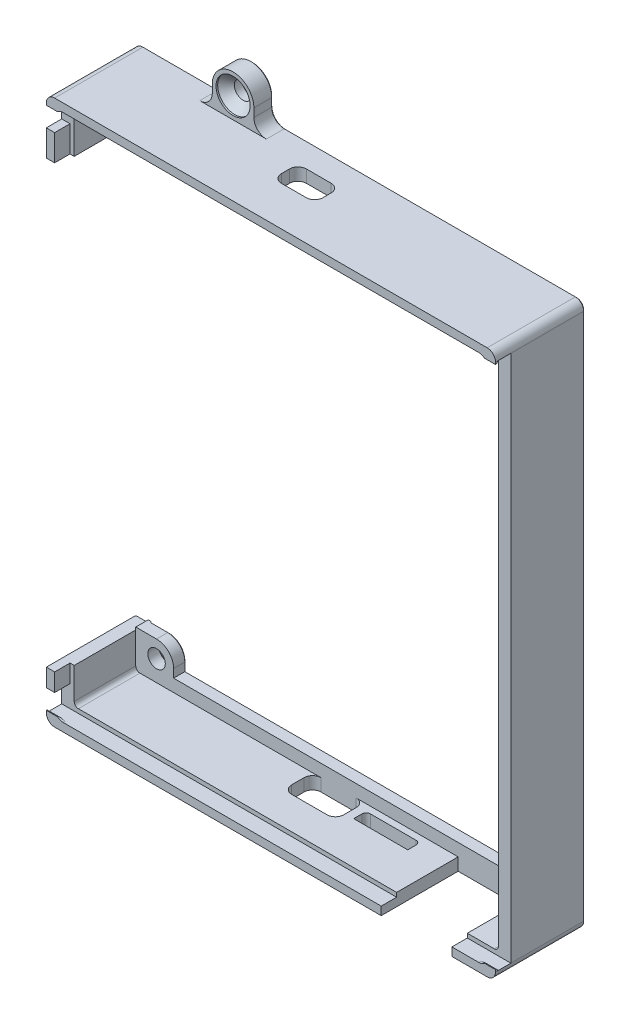
SolidWorks part; units mm, degrees
material "Custom Plastic"
ref_plane "Front Plane" through (0, 0, 0) normal (0, 0, 1) x (1, 0, 0)
ref_plane "Top Plane" through (0, 0, 0) normal (0, 1, 0) x (1, 0, 0)
ref_plane "Right Plane" through (0, 0, 0) normal (1, 0, 0) x (0, 0, -1)
sketch "Model" plane through (0, 0, 0) normal (0, 0, 1) x (1, 0, 0)
  line L0 (104.1673, 32.1811) -> (4.1672, 32.1811)
  line L1 (104.1673, 155.1806) -> (104.1673, 32.1811)
  line L2 (4.1672, 155.1806) -> (104.1673, 155.1806)
  line L3 (4.1672, 32.1811) -> (4.1672, 155.1806)
  line L4 (44.9158, 146.4259) -> (47.4224, 146.4259)
  line L5 (47.4224, 146.4259) -> (47.4224, 148.9326)
  line L6 (47.4224, 148.9326) -> (44.9158, 148.9326)
  line L7 (44.9158, 148.9326) -> (44.9158, 146.4259)
  line L8 (77.4127, 147.4278) -> (79.9193, 147.4278)
  line L9 (79.9193, 147.4278) -> (79.9193, 149.9344)
  line L10 (79.9193, 149.9344) -> (77.4127, 149.9344)
  line L11 (77.4127, 149.9344) -> (77.4127, 147.4278)
  line L12 (6.3266, 141.9721) -> (8.3592, 141.9721)
  line L13 (8.3592, 141.9721) -> (8.3592, 144.0047)
  line L14 (8.3592, 144.0047) -> (6.3266, 144.0047)
  line L15 (6.3266, 144.0047) -> (6.3266, 141.9721)
  line L16 (6.3266, 121.6529) -> (8.3592, 121.6529)
  line L17 (8.3592, 121.6529) -> (8.3592, 123.6855)
  line L18 (8.3592, 123.6855) -> (6.3266, 123.6855)
  line L19 (6.3266, 123.6855) -> (6.3266, 121.6529)
  line L20 (6.3266, 101.3324) -> (8.3592, 101.3324)
  line L21 (8.3592, 101.3324) -> (8.3592, 103.365)
  line L22 (8.3592, 103.365) -> (6.3266, 103.365)
  line L23 (6.3266, 103.365) -> (6.3266, 101.3324)
  line L24 (6.3266, 81.0118) -> (8.3592, 81.0118)
  line L25 (8.3592, 81.0118) -> (8.3592, 83.0444)
  line L26 (8.3592, 83.0444) -> (6.3266, 83.0444)
  line L27 (6.3266, 83.0444) -> (6.3266, 81.0118)
  line L28 (6.3266, 60.6927) -> (8.3592, 60.6927)
  line L29 (8.3592, 60.6927) -> (8.3592, 62.7253)
  line L30 (8.3592, 62.7253) -> (6.3266, 62.7253)
  line L31 (6.3266, 62.7253) -> (6.3266, 60.6927)
  line L32 (85.9221, 148.4144) -> (87.9547, 148.4144)
  line L33 (87.9547, 148.4144) -> (87.9547, 150.447)
  line L34 (87.9547, 150.447) -> (85.9221, 150.447)
  line L35 (85.9221, 150.447) -> (85.9221, 148.4144)
  line L36 (6.3266, 50.5324) -> (8.3592, 50.5324)
  line L37 (8.3592, 50.5324) -> (8.3592, 52.565)
  line L38 (8.3592, 52.565) -> (6.3266, 52.565)
  line L39 (6.3266, 52.565) -> (6.3266, 50.5324)
  line L40 (6.3266, 42.9118) -> (8.3592, 42.9118)
  line L41 (8.3592, 42.9118) -> (8.3592, 44.9444)
  line L42 (8.3592, 44.9444) -> (6.3266, 44.9444)
  line L43 (6.3266, 44.9444) -> (6.3266, 42.9118)
  line L44 (52.8726, 50.0418) -> (54.3815, 50.0418)
  line L45 (54.3815, 50.0418) -> (54.3815, 51.5508)
  line L46 (54.3815, 51.5508) -> (52.8726, 51.5508)
  line L47 (52.8726, 51.5508) -> (52.8726, 50.0418)
  line L48 (58.4219, 130.1637) -> (60.4545, 130.1637)
  line L49 (60.4545, 130.1637) -> (60.4545, 132.1963)
  line L50 (60.4545, 132.1963) -> (58.4219, 132.1963)
  line L51 (58.4219, 132.1963) -> (58.4219, 130.1637)
  line L52 (97.8807, 141.1439) -> (99.9133, 141.1439)
  line L53 (99.9133, 141.1439) -> (99.9133, 143.1765)
  line L54 (99.9133, 143.1765) -> (97.8807, 143.1765)
  line L55 (97.8807, 143.1765) -> (97.8807, 141.1439)
  line L56 (48.438, 37.3046) -> (48.438, 37.0552)
  line L57 (49.9456, 37.0552) -> (49.9456, 37.3046)
  line L58 (52.8877, 37.3046) -> (52.8877, 37.0552)
  line L59 (54.3967, 37.0552) -> (54.3967, 37.3046)
  line L60 (54.3126, 34.0993) -> (54.3126, 33.8995)
  line L61 (56.7201, 33.8995) -> (56.7201, 34.0993)
  line L62 (46.1133, 34.0993) -> (46.1133, 33.8995)
  line L63 (48.5207, 33.8995) -> (48.5207, 34.0993)
  line L64 (82.9607, 49.0165) -> (84.9933, 49.0165)
  line L65 (84.9933, 49.0165) -> (84.9933, 51.0492)
  line L66 (84.9933, 51.0492) -> (82.9607, 51.0492)
  line L67 (82.9607, 51.0492) -> (82.9607, 49.0165)
  line L68 (29.8828, 70.9163) -> (31.9154, 70.9163)
  line L69 (31.9154, 70.9163) -> (31.9154, 72.9489)
  line L70 (31.9154, 72.9489) -> (29.8828, 72.9489)
  line L71 (29.8828, 72.9489) -> (29.8828, 70.9163)
  line L72 (29.8828, 68.1658) -> (31.9154, 68.1658)
  line L73 (31.9154, 68.1658) -> (31.9154, 70.1984)
  line L74 (31.9154, 70.1984) -> (29.8828, 70.1984)
  line L75 (29.8828, 70.1984) -> (29.8828, 68.1658)
  line L76 (29.8828, 108.6649) -> (31.9154, 108.6649)
  line L77 (31.9154, 108.6649) -> (31.9154, 110.6975)
  line L78 (31.9154, 110.6975) -> (29.8828, 110.6975)
  line L79 (29.8828, 110.6975) -> (29.8828, 108.6649)
  line L80 (29.8828, 111.4141) -> (31.9154, 111.4141)
  line L81 (31.9154, 111.4141) -> (31.9154, 113.4467)
  line L82 (31.9154, 113.4467) -> (29.8828, 113.4467)
  line L83 (29.8828, 113.4467) -> (29.8828, 111.4141)
  line L84 (29.8828, 91.1652) -> (31.9154, 91.1652)
  line L85 (31.9154, 91.1652) -> (31.9154, 93.1978)
  line L86 (31.9154, 93.1978) -> (29.8828, 93.1978)
  line L87 (29.8828, 93.1978) -> (29.8828, 91.1652)
  line L88 (29.8828, 88.4147) -> (31.9154, 88.4147)
  line L89 (31.9154, 88.4147) -> (31.9154, 90.4473)
  line L90 (31.9154, 90.4473) -> (29.8828, 90.4473)
  line L91 (29.8828, 90.4473) -> (29.8828, 88.4147)
  line L92 (29.8828, 128.6658) -> (31.9154, 128.6658)
  line L93 (31.9154, 128.6658) -> (31.9154, 130.6984)
  line L94 (31.9154, 130.6984) -> (29.8828, 130.6984)
  line L95 (29.8828, 130.6984) -> (29.8828, 128.6658)
  line L96 (29.8828, 131.4163) -> (31.9154, 131.4163)
  line L97 (31.9154, 131.4163) -> (31.9154, 133.4489)
  line L98 (31.9154, 133.4489) -> (29.8828, 133.4489)
  line L99 (29.8828, 133.4489) -> (29.8828, 131.4163)
  line L100 (48.1611, 135.1453) -> (50.1937, 135.1453)
  line L101 (50.1937, 135.1453) -> (50.1937, 137.1779)
  line L102 (50.1937, 137.1779) -> (48.1611, 137.1779)
  line L103 (48.1611, 137.1779) -> (48.1611, 135.1453)
  line L104 (11.4074, 121.6529) -> (13.44, 121.6529)
  line L105 (13.44, 121.6529) -> (13.44, 123.6855)
  line L106 (13.44, 123.6855) -> (11.4074, 123.6855)
  line L107 (11.4074, 123.6855) -> (11.4074, 121.6529)
  line L108 (104.1673, 32.1811) -> (4.1672, 32.1811)
  line L109 (104.1673, 155.1806) -> (104.1673, 32.1811)
  line L110 (4.1672, 155.1806) -> (104.1673, 155.1806)
  line L111 (4.1672, 32.1811) -> (4.1672, 155.1806)
  spline S0 degree 3 poles (55.1711, 147.6799) (55.1711, 149.685) (52.1643, 149.685) (52.1643, 147.6799) knots 0 0 0 0 1 1 1 1
  spline S1 degree 3 poles (52.1643, 147.6799) (52.1643, 145.6749) (55.1711, 145.6749) (55.1711, 147.6799) knots 0 0 0 0 1 1 1 1
  spline S2 degree 3 poles (75.1706, 148.6804) (75.1706, 150.6854) (72.1637, 150.6854) (72.1637, 148.6804) knots 0 0 0 0 1 1 1 1
  spline S3 degree 3 poles (72.1637, 148.6804) (72.1637, 146.6754) (75.1706, 146.6754) (75.1706, 148.6804) knots 0 0 0 0 1 1 1 1
  spline S4 degree 3 poles (8.3592, 140.448) (8.3592, 141.8026) (6.3266, 141.8026) (6.3266, 140.448) knots 0 0 0 0 1 1 1 1
  spline S5 degree 3 poles (6.3266, 140.448) (6.3266, 139.0934) (8.3592, 139.0934) (8.3592, 140.448) knots 0 0 0 0 1 1 1 1
  spline S6 degree 3 poles (8.3592, 137.9083) (8.3592, 139.2629) (6.3266, 139.2629) (6.3266, 137.9083) knots 0 0 0 0 1 1 1 1
  spline S7 degree 3 poles (6.3266, 137.9083) (6.3266, 136.5537) (8.3592, 136.5537) (8.3592, 137.9083) knots 0 0 0 0 1 1 1 1
  spline S8 degree 3 poles (8.3592, 135.3686) (8.3592, 136.7232) (6.3266, 136.7232) (6.3266, 135.3686) knots 0 0 0 0 1 1 1 1
  spline S9 degree 3 poles (6.3266, 135.3686) (6.3266, 134.0139) (8.3592, 134.0139) (8.3592, 135.3686) knots 0 0 0 0 1 1 1 1
  spline S10 degree 3 poles (8.3592, 132.8288) (8.3592, 134.1834) (6.3266, 134.1834) (6.3266, 132.8288) knots 0 0 0 0 1 1 1 1
  spline S11 degree 3 poles (6.3266, 132.8288) (6.3266, 131.4742) (8.3592, 131.4742) (8.3592, 132.8288) knots 0 0 0 0 1 1 1 1
  spline S12 degree 3 poles (8.3592, 130.2891) (8.3592, 131.6437) (6.3266, 131.6437) (6.3266, 130.2891) knots 0 0 0 0 1 1 1 1
  spline S13 degree 3 poles (6.3266, 130.2891) (6.3266, 128.9331) (8.3592, 128.9331) (8.3592, 130.2891) knots 0 0 0 0 1 1 1 1
  spline S14 degree 3 poles (8.3592, 127.748) (8.3592, 129.1026) (6.3266, 129.1026) (6.3266, 127.748) knots 0 0 0 0 1 1 1 1
  spline S15 degree 3 poles (6.3266, 127.748) (6.3266, 126.3934) (8.3592, 126.3934) (8.3592, 127.748) knots 0 0 0 0 1 1 1 1
  spline S16 degree 3 poles (8.3592, 120.1288) (8.3592, 121.4834) (6.3266, 121.4834) (6.3266, 120.1288) knots 0 0 0 0 1 1 1 1
  spline S17 degree 3 poles (6.3266, 120.1288) (6.3266, 118.7742) (8.3592, 118.7742) (8.3592, 120.1288) knots 0 0 0 0 1 1 1 1
  spline S18 degree 3 poles (8.3592, 117.5891) (8.3592, 118.9437) (6.3266, 118.9437) (6.3266, 117.5891) knots 0 0 0 0 1 1 1 1
  spline S19 degree 3 poles (6.3266, 117.5891) (6.3266, 116.2331) (8.3592, 116.2331) (8.3592, 117.5891) knots 0 0 0 0 1 1 1 1
  spline S20 degree 3 poles (8.3592, 115.048) (8.3592, 116.4026) (6.3266, 116.4026) (6.3266, 115.048) knots 0 0 0 0 1 1 1 1
  spline S21 degree 3 poles (6.3266, 115.048) (6.3266, 113.6934) (8.3592, 113.6934) (8.3592, 115.048) knots 0 0 0 0 1 1 1 1
  spline S22 degree 3 poles (8.3592, 112.5083) (8.3592, 113.8629) (6.3266, 113.8629) (6.3266, 112.5083) knots 0 0 0 0 1 1 1 1
  spline S23 degree 3 poles (6.3266, 112.5083) (6.3266, 111.1537) (8.3592, 111.1537) (8.3592, 112.5083) knots 0 0 0 0 1 1 1 1
  spline S24 degree 3 poles (8.3592, 109.9686) (8.3592, 111.3232) (6.3266, 111.3232) (6.3266, 109.9686) knots 0 0 0 0 1 1 1 1
  spline S25 degree 3 poles (6.3266, 109.9686) (6.3266, 108.6139) (8.3592, 108.6139) (8.3592, 109.9686) knots 0 0 0 0 1 1 1 1
  spline S26 degree 3 poles (8.3592, 107.4288) (8.3592, 108.7834) (6.3266, 108.7834) (6.3266, 107.4288) knots 0 0 0 0 1 1 1 1
  spline S27 degree 3 poles (6.3266, 107.4288) (6.3266, 106.0742) (8.3592, 106.0742) (8.3592, 107.4288) knots 0 0 0 0 1 1 1 1
  spline S28 degree 3 poles (8.3592, 99.8083) (8.3592, 101.1629) (6.3266, 101.1629) (6.3266, 99.8083) knots 0 0 0 0 1 1 1 1
  spline S29 degree 3 poles (6.3266, 99.8083) (6.3266, 98.4537) (8.3592, 98.4537) (8.3592, 99.8083) knots 0 0 0 0 1 1 1 1
  spline S30 degree 3 poles (8.3592, 97.2686) (8.3592, 98.6232) (6.3266, 98.6232) (6.3266, 97.2686) knots 0 0 0 0 1 1 1 1
  spline S31 degree 3 poles (6.3266, 97.2686) (6.3266, 95.9139) (8.3592, 95.9139) (8.3592, 97.2686) knots 0 0 0 0 1 1 1 1
  spline S32 degree 3 poles (8.3592, 94.7288) (8.3592, 96.0834) (6.3266, 96.0834) (6.3266, 94.7288) knots 0 0 0 0 1 1 1 1
  spline S33 degree 3 poles (6.3266, 94.7288) (6.3266, 93.3742) (8.3592, 93.3742) (8.3592, 94.7288) knots 0 0 0 0 1 1 1 1
  spline S34 degree 3 poles (8.3592, 92.1891) (8.3592, 93.5437) (6.3266, 93.5437) (6.3266, 92.1891) knots 0 0 0 0 1 1 1 1
  spline S35 degree 3 poles (6.3266, 92.1891) (6.3266, 90.8331) (8.3592, 90.8331) (8.3592, 92.1891) knots 0 0 0 0 1 1 1 1
  spline S36 degree 3 poles (8.3592, 89.648) (8.3592, 91.0026) (6.3266, 91.0026) (6.3266, 89.648) knots 0 0 0 0 1 1 1 1
  spline S37 degree 3 poles (6.3266, 89.648) (6.3266, 88.2934) (8.3592, 88.2934) (8.3592, 89.648) knots 0 0 0 0 1 1 1 1
  spline S38 degree 3 poles (8.3592, 87.1083) (8.3592, 88.4629) (6.3266, 88.4629) (6.3266, 87.1083) knots 0 0 0 0 1 1 1 1
  spline S39 degree 3 poles (6.3266, 87.1083) (6.3266, 85.7537) (8.3592, 85.7537) (8.3592, 87.1083) knots 0 0 0 0 1 1 1 1
  spline S40 degree 3 poles (8.3592, 79.4891) (8.3592, 80.8437) (6.3266, 80.8437) (6.3266, 79.4891) knots 0 0 0 0 1 1 1 1
  spline S41 degree 3 poles (6.3266, 79.4891) (6.3266, 78.1331) (8.3592, 78.1331) (8.3592, 79.4891) knots 0 0 0 0 1 1 1 1
  spline S42 degree 3 poles (8.3592, 76.948) (8.3592, 78.3026) (6.3266, 78.3026) (6.3266, 76.948) knots 0 0 0 0 1 1 1 1
  spline S43 degree 3 poles (6.3266, 76.948) (6.3266, 75.5934) (8.3592, 75.5934) (8.3592, 76.948) knots 0 0 0 0 1 1 1 1
  spline S44 degree 3 poles (8.3592, 74.4083) (8.3592, 75.7629) (6.3266, 75.7629) (6.3266, 74.4083) knots 0 0 0 0 1 1 1 1
  spline S45 degree 3 poles (6.3266, 74.4083) (6.3266, 73.0537) (8.3592, 73.0537) (8.3592, 74.4083) knots 0 0 0 0 1 1 1 1
  spline S46 degree 3 poles (8.3592, 71.8685) (8.3592, 73.2232) (6.3266, 73.2232) (6.3266, 71.8685) knots 0 0 0 0 1 1 1 1
  spline S47 degree 3 poles (6.3266, 71.8685) (6.3266, 70.5139) (8.3592, 70.5139) (8.3592, 71.8685) knots 0 0 0 0 1 1 1 1
  spline S48 degree 3 poles (8.3592, 69.3288) (8.3592, 70.6834) (6.3266, 70.6834) (6.3266, 69.3288) knots 0 0 0 0 1 1 1 1
  spline S49 degree 3 poles (6.3266, 69.3288) (6.3266, 67.9742) (8.3592, 67.9742) (8.3592, 69.3288) knots 0 0 0 0 1 1 1 1
  spline S50 degree 3 poles (8.3592, 66.7891) (8.3592, 68.1437) (6.3266, 68.1437) (6.3266, 66.7891) knots 0 0 0 0 1 1 1 1
  spline S51 degree 3 poles (6.3266, 66.7891) (6.3266, 65.4331) (8.3592, 65.4331) (8.3592, 66.7891) knots 0 0 0 0 1 1 1 1
  spline S52 degree 3 poles (8.3592, 59.1686) (8.3592, 60.5232) (6.3266, 60.5232) (6.3266, 59.1686) knots 0 0 0 0 1 1 1 1
  spline S53 degree 3 poles (6.3266, 59.1686) (6.3266, 57.8139) (8.3592, 57.8139) (8.3592, 59.1686) knots 0 0 0 0 1 1 1 1
  spline S54 degree 3 poles (8.3592, 56.6288) (8.3592, 57.9834) (6.3266, 57.9834) (6.3266, 56.6288) knots 0 0 0 0 1 1 1 1
  spline S55 degree 3 poles (6.3266, 56.6288) (6.3266, 55.2742) (8.3592, 55.2742) (8.3592, 56.6288) knots 0 0 0 0 1 1 1 1
  spline S56 degree 3 poles (8.3592, 54.0891) (8.3592, 55.4437) (6.3266, 55.4437) (6.3266, 54.0891) knots 0 0 0 0 1 1 1 1
  spline S57 degree 3 poles (6.3266, 54.0891) (6.3266, 52.7331) (8.3592, 52.7331) (8.3592, 54.0891) knots 0 0 0 0 1 1 1 1
  spline S58 degree 3 poles (85.4149, 149.4301) (85.4149, 150.7847) (83.3823, 150.7847) (83.3823, 149.4301) knots 0 0 0 0 1 1 1 1
  spline S59 degree 3 poles (83.3823, 149.4301) (83.3823, 148.0754) (85.4149, 148.0754) (85.4149, 149.4301) knots 0 0 0 0 1 1 1 1
  spline S60 degree 3 poles (8.3592, 49.0083) (8.3592, 50.3629) (6.3266, 50.3629) (6.3266, 49.0083) knots 0 0 0 0 1 1 1 1
  spline S61 degree 3 poles (6.3266, 49.0083) (6.3266, 47.6537) (8.3592, 47.6537) (8.3592, 49.0083) knots 0 0 0 0 1 1 1 1
  spline S62 degree 3 poles (8.3592, 41.3891) (8.3592, 42.7437) (6.3266, 42.7437) (6.3266, 41.3891) knots 0 0 0 0 1 1 1 1
  spline S63 degree 3 poles (6.3266, 41.3891) (6.3266, 40.0331) (8.3592, 40.0331) (8.3592, 41.3891) knots 0 0 0 0 1 1 1 1
  spline S64 degree 3 poles (54.3815, 52.0661) (54.3815, 53.0721) (52.8726, 53.0721) (52.8726, 52.0661) knots 0 0 0 0 1 1 1 1
  spline S65 degree 3 poles (52.8726, 52.0661) (52.8726, 51.0602) (54.3815, 51.0602) (54.3815, 52.0661) knots 0 0 0 0 1 1 1 1
  spline S66 degree 3 poles (55.6507, 50.797) (55.6507, 51.8029) (54.1417, 51.8029) (54.1417, 50.797) knots 0 0 0 0 1 1 1 1
  spline S67 degree 3 poles (54.1417, 50.797) (54.1417, 49.791) (55.6507, 49.791) (55.6507, 50.797) knots 0 0 0 0 1 1 1 1
  spline S68 degree 3 poles (55.6507, 52.0661) (55.6507, 53.0721) (54.1417, 53.0721) (54.1417, 52.0661) knots 0 0 0 0 1 1 1 1
  spline S69 degree 3 poles (54.1417, 52.0661) (54.1417, 51.0602) (55.6507, 51.0602) (55.6507, 52.0661) knots 0 0 0 0 1 1 1 1
  spline S70 degree 3 poles (56.9212, 50.797) (56.9212, 51.8029) (55.4123, 51.8029) (55.4123, 50.797) knots 0 0 0 0 1 1 1 1
  spline S71 degree 3 poles (55.4123, 50.797) (55.4123, 49.791) (56.9212, 49.791) (56.9212, 50.797) knots 0 0 0 0 1 1 1 1
  spline S72 degree 3 poles (56.9212, 52.0661) (56.9212, 53.0721) (55.4123, 53.0721) (55.4123, 52.0661) knots 0 0 0 0 1 1 1 1
  spline S73 degree 3 poles (55.4123, 52.0661) (55.4123, 51.0602) (56.9212, 51.0602) (56.9212, 52.0661) knots 0 0 0 0 1 1 1 1
  spline S74 degree 3 poles (58.1904, 50.797) (58.1904, 51.8029) (56.6828, 51.8029) (56.6828, 50.797) knots 0 0 0 0 1 1 1 1
  spline S75 degree 3 poles (56.6828, 50.797) (56.6828, 49.791) (58.1904, 49.791) (58.1904, 50.797) knots 0 0 0 0 1 1 1 1
  spline S76 degree 3 poles (58.1904, 52.0661) (58.1904, 53.0721) (56.6828, 53.0721) (56.6828, 52.0661) knots 0 0 0 0 1 1 1 1
  spline S77 degree 3 poles (56.6828, 52.0661) (56.6828, 51.0602) (58.1904, 51.0602) (58.1904, 52.0661) knots 0 0 0 0 1 1 1 1
  spline S78 degree 3 poles (59.461, 50.797) (59.461, 51.8029) (57.952, 51.8029) (57.952, 50.797) knots 0 0 0 0 1 1 1 1
  spline S79 degree 3 poles (57.952, 50.797) (57.952, 49.791) (59.461, 49.791) (59.461, 50.797) knots 0 0 0 0 1 1 1 1
  spline S80 degree 3 poles (59.461, 52.0661) (59.461, 53.0721) (57.952, 53.0721) (57.952, 52.0661) knots 0 0 0 0 1 1 1 1
  spline S81 degree 3 poles (57.952, 52.0661) (57.952, 51.0602) (59.461, 51.0602) (59.461, 52.0661) knots 0 0 0 0 1 1 1 1
  spline S82 degree 3 poles (57.9148, 131.1793) (57.9148, 132.5353) (55.8822, 132.5353) (55.8822, 131.1793) knots 0 0 0 0 1 1 1 1
  spline S83 degree 3 poles (55.8822, 131.1793) (55.8822, 129.8247) (57.9148, 129.8247) (57.9148, 131.1793) knots 0 0 0 0 1 1 1 1
  spline S84 degree 3 poles (63.2437, 36.9311) (63.2437, 37.9371) (61.7347, 37.9371) (61.7347, 36.9311) knots 0 0 0 0 1 1 1 1
  spline S85 degree 3 poles (61.7347, 36.9311) (61.7347, 35.9252) (63.2437, 35.9252) (63.2437, 36.9311) knots 0 0 0 0 1 1 1 1
  spline S86 degree 3 poles (71.2239, 36.9311) (71.2239, 37.9371) (69.715, 37.9371) (69.715, 36.9311) knots 0 0 0 0 1 1 1 1
  spline S87 degree 3 poles (69.715, 36.9311) (69.715, 35.9252) (71.2239, 35.9252) (71.2239, 36.9311) knots 0 0 0 0 1 1 1 1
  spline S88 degree 3 poles (102.453, 142.1609) (102.453, 143.5155) (100.4204, 143.5155) (100.4204, 142.1609) knots 0 0 0 0 1 1 1 1
  spline S89 degree 3 poles (100.4204, 142.1609) (100.4204, 140.8063) (102.453, 140.8063) (102.453, 142.1609) knots 0 0 0 0 1 1 1 1
  spline S90 degree 3 poles (99.9133, 129.4609) (99.9133, 130.8155) (97.8807, 130.8155) (97.8807, 129.4609) knots 0 0 0 0 1 1 1 1
  spline S91 degree 3 poles (97.8807, 129.4609) (97.8807, 128.1063) (99.9133, 128.1063) (99.9133, 129.4609) knots 0 0 0 0 1 1 1 1
  spline S92 degree 3 poles (102.453, 139.6198) (102.453, 140.9744) (100.4204, 140.9744) (100.4204, 139.6198) knots 0 0 0 0 1 1 1 1
  spline S93 degree 3 poles (100.4204, 139.6198) (100.4204, 138.2652) (102.453, 138.2652) (102.453, 139.6198) knots 0 0 0 0 1 1 1 1
  spline S94 degree 3 poles (99.9133, 126.9198) (99.9133, 128.2744) (97.8807, 128.2744) (97.8807, 126.9198) knots 0 0 0 0 1 1 1 1
  spline S95 degree 3 poles (97.8807, 126.9198) (97.8807, 125.5652) (99.9133, 125.5652) (99.9133, 126.9198) knots 0 0 0 0 1 1 1 1
  spline S96 degree 3 poles (102.453, 137.0801) (102.453, 138.4347) (100.4204, 138.4347) (100.4204, 137.0801) knots 0 0 0 0 1 1 1 1
  spline S97 degree 3 poles (100.4204, 137.0801) (100.4204, 135.7255) (102.453, 135.7255) (102.453, 137.0801) knots 0 0 0 0 1 1 1 1
  spline S98 degree 3 poles (99.9133, 124.3801) (99.9133, 125.7347) (97.8807, 125.7347) (97.8807, 124.3801) knots 0 0 0 0 1 1 1 1
  spline S99 degree 3 poles (97.8807, 124.3801) (97.8807, 123.0255) (99.9133, 123.0255) (99.9133, 124.3801) knots 0 0 0 0 1 1 1 1
  spline S100 degree 3 poles (102.453, 134.5403) (102.453, 135.895) (100.4204, 135.895) (100.4204, 134.5403) knots 0 0 0 0 1 1 1 1
  spline S101 degree 3 poles (100.4204, 134.5403) (100.4204, 133.1857) (102.453, 133.1857) (102.453, 134.5403) knots 0 0 0 0 1 1 1 1
  spline S102 degree 3 poles (99.9133, 121.8404) (99.9133, 123.195) (97.8807, 123.195) (97.8807, 121.8404) knots 0 0 0 0 1 1 1 1
  spline S103 degree 3 poles (97.8807, 121.8404) (97.8807, 120.4857) (99.9133, 120.4857) (99.9133, 121.8404) knots 0 0 0 0 1 1 1 1
  spline S104 degree 3 poles (102.453, 132.0006) (102.453, 133.3552) (100.4204, 133.3552) (100.4204, 132.0006) knots 0 0 0 0 1 1 1 1
  spline S105 degree 3 poles (100.4204, 132.0006) (100.4204, 130.646) (102.453, 130.646) (102.453, 132.0006) knots 0 0 0 0 1 1 1 1
  spline S106 degree 3 poles (99.9133, 119.3006) (99.9133, 120.6552) (97.8807, 120.6552) (97.8807, 119.3006) knots 0 0 0 0 1 1 1 1
  spline S107 degree 3 poles (97.8807, 119.3006) (97.8807, 117.946) (99.9133, 117.946) (99.9133, 119.3006) knots 0 0 0 0 1 1 1 1
  spline S108 degree 3 poles (102.453, 129.4609) (102.453, 130.8155) (100.4204, 130.8155) (100.4204, 129.4609) knots 0 0 0 0 1 1 1 1
  spline S109 degree 3 poles (100.4204, 129.4609) (100.4204, 128.1063) (102.453, 128.1063) (102.453, 129.4609) knots 0 0 0 0 1 1 1 1
  spline S110 degree 3 poles (99.9133, 116.7609) (99.9133, 118.1155) (97.8807, 118.1155) (97.8807, 116.7609) knots 0 0 0 0 1 1 1 1
  spline S111 degree 3 poles (97.8807, 116.7609) (97.8807, 115.4063) (99.9133, 115.4063) (99.9133, 116.7609) knots 0 0 0 0 1 1 1 1
  spline S112 degree 3 poles (102.453, 126.9198) (102.453, 128.2744) (100.4204, 128.2744) (100.4204, 126.9198) knots 0 0 0 0 1 1 1 1
  spline S113 degree 3 poles (100.4204, 126.9198) (100.4204, 125.5652) (102.453, 125.5652) (102.453, 126.9198) knots 0 0 0 0 1 1 1 1
  spline S114 degree 3 poles (99.9133, 114.2198) (99.9133, 115.5744) (97.8807, 115.5744) (97.8807, 114.2198) knots 0 0 0 0 1 1 1 1
  spline S115 degree 3 poles (97.8807, 114.2198) (97.8807, 112.8652) (99.9133, 112.8652) (99.9133, 114.2198) knots 0 0 0 0 1 1 1 1
  spline S116 degree 3 poles (102.453, 124.3801) (102.453, 125.7347) (100.4204, 125.7347) (100.4204, 124.3801) knots 0 0 0 0 1 1 1 1
  spline S117 degree 3 poles (100.4204, 124.3801) (100.4204, 123.0255) (102.453, 123.0255) (102.453, 124.3801) knots 0 0 0 0 1 1 1 1
  spline S118 degree 3 poles (99.9133, 111.6801) (99.9133, 113.0347) (97.8807, 113.0347) (97.8807, 111.6801) knots 0 0 0 0 1 1 1 1
  spline S119 degree 3 poles (97.8807, 111.6801) (97.8807, 110.3255) (99.9133, 110.3255) (99.9133, 111.6801) knots 0 0 0 0 1 1 1 1
  spline S120 degree 3 poles (102.453, 121.8404) (102.453, 123.195) (100.4204, 123.195) (100.4204, 121.8404) knots 0 0 0 0 1 1 1 1
  spline S121 degree 3 poles (100.4204, 121.8404) (100.4204, 120.4857) (102.453, 120.4857) (102.453, 121.8404) knots 0 0 0 0 1 1 1 1
  spline S122 degree 3 poles (99.9133, 109.1404) (99.9133, 110.495) (97.8807, 110.495) (97.8807, 109.1404) knots 0 0 0 0 1 1 1 1
  spline S123 degree 3 poles (97.8807, 109.1404) (97.8807, 107.7857) (99.9133, 107.7857) (99.9133, 109.1404) knots 0 0 0 0 1 1 1 1
  spline S124 degree 3 poles (102.453, 119.3006) (102.453, 120.6552) (100.4204, 120.6552) (100.4204, 119.3006) knots 0 0 0 0 1 1 1 1
  spline S125 degree 3 poles (100.4204, 119.3006) (100.4204, 117.946) (102.453, 117.946) (102.453, 119.3006) knots 0 0 0 0 1 1 1 1
  spline S126 degree 3 poles (99.9133, 106.6006) (99.9133, 107.9552) (97.8807, 107.9552) (97.8807, 106.6006) knots 0 0 0 0 1 1 1 1
  spline S127 degree 3 poles (97.8807, 106.6006) (97.8807, 105.246) (99.9133, 105.246) (99.9133, 106.6006) knots 0 0 0 0 1 1 1 1
  spline S128 degree 3 poles (102.453, 116.7609) (102.453, 118.1155) (100.4204, 118.1155) (100.4204, 116.7609) knots 0 0 0 0 1 1 1 1
  spline S129 degree 3 poles (100.4204, 116.7609) (100.4204, 115.4063) (102.453, 115.4063) (102.453, 116.7609) knots 0 0 0 0 1 1 1 1
  spline S130 degree 3 poles (99.9133, 104.0609) (99.9133, 105.4155) (97.8807, 105.4155) (97.8807, 104.0609) knots 0 0 0 0 1 1 1 1
  spline S131 degree 3 poles (97.8807, 104.0609) (97.8807, 102.7063) (99.9133, 102.7063) (99.9133, 104.0609) knots 0 0 0 0 1 1 1 1
  spline S132 degree 3 poles (102.453, 114.2198) (102.453, 115.5744) (100.4204, 115.5744) (100.4204, 114.2198) knots 0 0 0 0 1 1 1 1
  spline S133 degree 3 poles (100.4204, 114.2198) (100.4204, 112.8652) (102.453, 112.8652) (102.453, 114.2198) knots 0 0 0 0 1 1 1 1
  spline S134 degree 3 poles (102.453, 111.6801) (102.453, 113.0347) (100.4204, 113.0347) (100.4204, 111.6801) knots 0 0 0 0 1 1 1 1
  spline S135 degree 3 poles (100.4204, 111.6801) (100.4204, 110.3255) (102.453, 110.3255) (102.453, 111.6801) knots 0 0 0 0 1 1 1 1
  spline S136 degree 3 poles (99.9133, 101.5198) (99.9133, 102.8744) (97.8807, 102.8744) (97.8807, 101.5198) knots 0 0 0 0 1 1 1 1
  spline S137 degree 3 poles (97.8807, 101.5198) (97.8807, 100.1652) (99.9133, 100.1652) (99.9133, 101.5198) knots 0 0 0 0 1 1 1 1
  spline S138 degree 3 poles (102.453, 109.1404) (102.453, 110.495) (100.4204, 110.495) (100.4204, 109.1404) knots 0 0 0 0 1 1 1 1
  spline S139 degree 3 poles (100.4204, 109.1404) (100.4204, 107.7857) (102.453, 107.7857) (102.453, 109.1404) knots 0 0 0 0 1 1 1 1
  spline S140 degree 3 poles (102.453, 104.0609) (102.453, 105.4155) (100.4204, 105.4155) (100.4204, 104.0609) knots 0 0 0 0 1 1 1 1
  spline S141 degree 3 poles (100.4204, 104.0609) (100.4204, 102.7063) (102.453, 102.7063) (102.453, 104.0609) knots 0 0 0 0 1 1 1 1
  spline S142 degree 3 poles (102.453, 101.5198) (102.453, 102.8744) (100.4204, 102.8744) (100.4204, 101.5198) knots 0 0 0 0 1 1 1 1
  spline S143 degree 3 poles (100.4204, 101.5198) (100.4204, 100.1652) (102.453, 100.1652) (102.453, 101.5198) knots 0 0 0 0 1 1 1 1
  spline S144 degree 3 poles (102.453, 98.9801) (102.453, 100.3347) (100.4204, 100.3347) (100.4204, 98.9801) knots 0 0 0 0 1 1 1 1
  spline S145 degree 3 poles (100.4204, 98.9801) (100.4204, 97.6255) (102.453, 97.6255) (102.453, 98.9801) knots 0 0 0 0 1 1 1 1
  spline S146 degree 3 poles (102.453, 96.4404) (102.453, 97.795) (100.4204, 97.795) (100.4204, 96.4404) knots 0 0 0 0 1 1 1 1
  spline S147 degree 3 poles (100.4204, 96.4404) (100.4204, 95.0857) (102.453, 95.0857) (102.453, 96.4404) knots 0 0 0 0 1 1 1 1
  spline S148 degree 3 poles (99.9133, 98.9801) (99.9133, 100.3347) (97.8807, 100.3347) (97.8807, 98.9801) knots 0 0 0 0 1 1 1 1
  spline S149 degree 3 poles (97.8807, 98.9801) (97.8807, 97.6255) (99.9133, 97.6255) (99.9133, 98.9801) knots 0 0 0 0 1 1 1 1
  spline S150 degree 3 poles (99.9133, 96.4404) (99.9133, 97.795) (97.8807, 97.795) (97.8807, 96.4404) knots 0 0 0 0 1 1 1 1
  spline S151 degree 3 poles (97.8807, 96.4404) (97.8807, 95.0857) (99.9133, 95.0857) (99.9133, 96.4404) knots 0 0 0 0 1 1 1 1
  spline S152 degree 3 poles (99.9133, 139.6198) (99.9133, 140.9744) (97.8807, 140.9744) (97.8807, 139.6198) knots 0 0 0 0 1 1 1 1
  spline S153 degree 3 poles (97.8807, 139.6198) (97.8807, 138.2652) (99.9133, 138.2652) (99.9133, 139.6198) knots 0 0 0 0 1 1 1 1
  spline S154 degree 3 poles (99.9133, 137.0801) (99.9133, 138.4347) (97.8807, 138.4347) (97.8807, 137.0801) knots 0 0 0 0 1 1 1 1
  spline S155 degree 3 poles (97.8807, 137.0801) (97.8807, 135.7255) (99.9133, 135.7255) (99.9133, 137.0801) knots 0 0 0 0 1 1 1 1
  spline S156 degree 3 poles (99.9133, 134.5403) (99.9133, 135.895) (97.8807, 135.895) (97.8807, 134.5403) knots 0 0 0 0 1 1 1 1
  spline S157 degree 3 poles (97.8807, 134.5403) (97.8807, 133.1857) (99.9133, 133.1857) (99.9133, 134.5403) knots 0 0 0 0 1 1 1 1
  spline S158 degree 3 poles (99.9133, 132.0006) (99.9133, 133.3552) (97.8807, 133.3552) (97.8807, 132.0006) knots 0 0 0 0 1 1 1 1
  spline S159 degree 3 poles (97.8807, 132.0006) (97.8807, 130.646) (99.9133, 130.646) (99.9133, 132.0006) knots 0 0 0 0 1 1 1 1
  spline S160 degree 3 poles (99.9133, 93.9006) (99.9133, 95.2552) (97.8807, 95.2552) (97.8807, 93.9006) knots 0 0 0 0 1 1 1 1
  spline S161 degree 3 poles (97.8807, 93.9006) (97.8807, 92.546) (99.9133, 92.546) (99.9133, 93.9006) knots 0 0 0 0 1 1 1 1
  spline S162 degree 3 poles (102.453, 93.9006) (102.453, 95.2552) (100.4204, 95.2552) (100.4204, 93.9006) knots 0 0 0 0 1 1 1 1
  spline S163 degree 3 poles (100.4204, 93.9006) (100.4204, 92.546) (102.453, 92.546) (102.453, 93.9006) knots 0 0 0 0 1 1 1 1
  spline S164 degree 3 poles (102.453, 106.6006) (102.453, 107.9552) (100.4204, 107.9552) (100.4204, 106.6006) knots 0 0 0 0 1 1 1 1
  spline S165 degree 3 poles (100.4204, 106.6006) (100.4204, 105.246) (102.453, 105.246) (102.453, 106.6006) knots 0 0 0 0 1 1 1 1
  spline S166 degree 3 poles (99.9133, 91.3609) (99.9133, 92.7155) (97.8807, 92.7155) (97.8807, 91.3609) knots 0 0 0 0 1 1 1 1
  spline S167 degree 3 poles (97.8807, 91.3609) (97.8807, 90.0063) (99.9133, 90.0063) (99.9133, 91.3609) knots 0 0 0 0 1 1 1 1
  spline S168 degree 3 poles (102.453, 91.3609) (102.453, 92.7155) (100.4204, 92.7155) (100.4204, 91.3609) knots 0 0 0 0 1 1 1 1
  spline S169 degree 3 poles (100.4204, 91.3609) (100.4204, 90.0063) (102.453, 90.0063) (102.453, 91.3609) knots 0 0 0 0 1 1 1 1
  spline S170 degree 3 poles (99.9133, 88.8198) (99.9133, 90.1744) (97.8807, 90.1744) (97.8807, 88.8198) knots 0 0 0 0 1 1 1 1
  spline S171 degree 3 poles (97.8807, 88.8198) (97.8807, 87.4652) (99.9133, 87.4652) (99.9133, 88.8198) knots 0 0 0 0 1 1 1 1
  spline S172 degree 3 poles (102.453, 88.8198) (102.453, 90.1744) (100.4204, 90.1744) (100.4204, 88.8198) knots 0 0 0 0 1 1 1 1
  spline S173 degree 3 poles (100.4204, 88.8198) (100.4204, 87.4652) (102.453, 87.4652) (102.453, 88.8198) knots 0 0 0 0 1 1 1 1
  spline S174 degree 3 poles (99.9133, 86.2801) (99.9133, 87.6347) (97.8807, 87.6347) (97.8807, 86.2801) knots 0 0 0 0 1 1 1 1
  spline S175 degree 3 poles (97.8807, 86.2801) (97.8807, 84.9255) (99.9133, 84.9255) (99.9133, 86.2801) knots 0 0 0 0 1 1 1 1
  spline S176 degree 3 poles (102.453, 86.2801) (102.453, 87.6347) (100.4204, 87.6347) (100.4204, 86.2801) knots 0 0 0 0 1 1 1 1
  spline S177 degree 3 poles (100.4204, 86.2801) (100.4204, 84.9255) (102.453, 84.9255) (102.453, 86.2801) knots 0 0 0 0 1 1 1 1
  spline S178 degree 3 poles (99.9133, 83.7404) (99.9133, 85.095) (97.8807, 85.095) (97.8807, 83.7404) knots 0 0 0 0 1 1 1 1
  spline S179 degree 3 poles (97.8807, 83.7404) (97.8807, 82.3857) (99.9133, 82.3857) (99.9133, 83.7404) knots 0 0 0 0 1 1 1 1
  spline S180 degree 3 poles (102.453, 83.7404) (102.453, 85.095) (100.4204, 85.095) (100.4204, 83.7404) knots 0 0 0 0 1 1 1 1
  spline S181 degree 3 poles (100.4204, 83.7404) (100.4204, 82.3857) (102.453, 82.3857) (102.453, 83.7404) knots 0 0 0 0 1 1 1 1
  spline S182 degree 3 poles (99.9133, 81.2006) (99.9133, 82.5552) (97.8807, 82.5552) (97.8807, 81.2006) knots 0 0 0 0 1 1 1 1
  spline S183 degree 3 poles (97.8807, 81.2006) (97.8807, 79.846) (99.9133, 79.846) (99.9133, 81.2006) knots 0 0 0 0 1 1 1 1
  spline S184 degree 3 poles (102.453, 81.2006) (102.453, 82.5552) (100.4204, 82.5552) (100.4204, 81.2006) knots 0 0 0 0 1 1 1 1
  spline S185 degree 3 poles (100.4204, 81.2006) (100.4204, 79.846) (102.453, 79.846) (102.453, 81.2006) knots 0 0 0 0 1 1 1 1
  spline S186 degree 3 poles (49.9456, 37.3046) (49.9456, 38.3106) (48.438, 38.3106) (48.438, 37.3046) knots 0 0 0 0 1 1 1 1
  spline S187 degree 3 poles (48.438, 37.0552) (48.438, 36.0492) (49.9456, 36.0492) (49.9456, 37.0552) knots 0 0 0 0 1 1 1 1
  spline S188 degree 3 poles (54.3967, 37.3046) (54.3967, 38.3106) (52.8877, 38.3106) (52.8877, 37.3046) knots 0 0 0 0 1 1 1 1
  spline S189 degree 3 poles (52.8877, 37.0552) (52.8877, 36.0492) (54.3967, 36.0492) (54.3967, 37.0552) knots 0 0 0 0 1 1 1 1
  spline S190 degree 3 poles (56.7201, 34.0993) (56.7201, 35.7047) (54.3126, 35.7047) (54.3126, 34.0993) knots 0 0 0 0 1 1 1 1
  spline S191 degree 3 poles (54.3126, 33.8995) (54.3126, 32.2941) (56.7201, 32.2941) (56.7201, 33.8995) knots 0 0 0 0 1 1 1 1
  spline S192 degree 3 poles (48.5207, 34.0993) (48.5207, 35.7047) (46.1133, 35.7047) (46.1133, 34.0993) knots 0 0 0 0 1 1 1 1
  spline S193 degree 3 poles (46.1133, 33.8995) (46.1133, 32.2941) (48.5207, 32.2941) (48.5207, 33.8995) knots 0 0 0 0 1 1 1 1
  spline S194 degree 3 poles (54.4711, 34.0001) (54.4711, 34.9054) (53.1123, 34.9054) (53.1123, 34.0001) knots 0 0 0 0 1 1 1 1
  spline S195 degree 3 poles (53.1123, 34.0001) (53.1123, 33.0933) (54.4711, 33.0933) (54.4711, 34.0001) knots 0 0 0 0 1 1 1 1
  spline S196 degree 3 poles (49.721, 34.0001) (49.721, 34.9054) (48.3623, 34.9054) (48.3623, 34.0001) knots 0 0 0 0 1 1 1 1
  spline S197 degree 3 poles (48.3623, 34.0001) (48.3623, 33.0933) (49.721, 33.0933) (49.721, 34.0001) knots 0 0 0 0 1 1 1 1
  spline S198 degree 3 poles (84.606, 43.6822) (84.606, 46.2205) (80.7985, 46.2205) (80.7985, 43.6822) knots 0 0 0 0 1 1 1 1
  spline S199 degree 3 poles (80.7985, 43.6822) (80.7985, 41.1438) (84.606, 41.1438) (84.606, 43.6822) knots 0 0 0 0 1 1 1 1
  spline S200 degree 3 poles (96.0355, 43.6822) (96.0355, 46.2205) (92.228, 46.2205) (92.228, 43.6822) knots 0 0 0 0 1 1 1 1
  spline S201 degree 3 poles (92.228, 43.6822) (92.228, 41.1438) (96.0355, 41.1438) (96.0355, 43.6822) knots 0 0 0 0 1 1 1 1
  spline S202 degree 3 poles (93.8775, 52.5719) (93.8775, 53.9265) (91.8462, 53.9265) (91.8462, 52.5719) knots 0 0 0 0 1 1 1 1
  spline S203 degree 3 poles (91.8462, 52.5719) (91.8462, 51.2173) (93.8775, 51.2173) (93.8775, 52.5719) knots 0 0 0 0 1 1 1 1
  spline S204 degree 3 poles (92.6124, 50.0322) (92.6124, 51.3868) (90.5812, 51.3868) (90.5812, 50.0322) knots 0 0 0 0 1 1 1 1
  spline S205 degree 3 poles (90.5812, 50.0322) (90.5812, 48.6775) (92.6124, 48.6775) (92.6124, 50.0322) knots 0 0 0 0 1 1 1 1
  spline S206 degree 3 poles (91.3377, 52.5719) (91.3377, 53.9265) (89.3065, 53.9265) (89.3065, 52.5719) knots 0 0 0 0 1 1 1 1
  spline S207 degree 3 poles (89.3065, 52.5719) (89.3065, 51.2173) (91.3377, 51.2173) (91.3377, 52.5719) knots 0 0 0 0 1 1 1 1
  spline S208 degree 3 poles (90.0727, 50.0322) (90.0727, 51.3868) (88.0415, 51.3868) (88.0415, 50.0322) knots 0 0 0 0 1 1 1 1
  spline S209 degree 3 poles (88.0415, 50.0322) (88.0415, 48.6775) (90.0727, 48.6775) (90.0727, 50.0322) knots 0 0 0 0 1 1 1 1
  spline S210 degree 3 poles (88.798, 52.5719) (88.798, 53.9265) (86.7654, 53.9265) (86.7654, 52.5719) knots 0 0 0 0 1 1 1 1
  spline S211 degree 3 poles (86.7654, 52.5719) (86.7654, 51.2173) (88.798, 51.2173) (88.798, 52.5719) knots 0 0 0 0 1 1 1 1
  spline S212 degree 3 poles (87.533, 50.0322) (87.533, 51.3868) (85.5018, 51.3868) (85.5018, 50.0322) knots 0 0 0 0 1 1 1 1
  spline S213 degree 3 poles (85.5018, 50.0322) (85.5018, 48.6775) (87.533, 48.6775) (87.533, 50.0322) knots 0 0 0 0 1 1 1 1
  spline S214 degree 3 poles (86.2583, 52.5719) (86.2583, 53.9265) (84.2257, 53.9265) (84.2257, 52.5719) knots 0 0 0 0 1 1 1 1
  spline S215 degree 3 poles (84.2257, 52.5719) (84.2257, 51.2173) (86.2583, 51.2173) (86.2583, 52.5719) knots 0 0 0 0 1 1 1 1
  spline S216 degree 3 poles (82.1945, 46.7331) (82.1945, 48.7644) (79.1462, 48.7644) (79.1462, 46.7331) knots 0 0 0 0 1 1 1 1
  spline S217 degree 3 poles (79.1462, 46.7331) (79.1462, 44.7005) (82.1945, 44.7005) (82.1945, 46.7331) knots 0 0 0 0 1 1 1 1
  spline S218 degree 3 poles (97.6877, 46.7304) (97.6877, 48.7616) (94.6395, 48.7616) (94.6395, 46.7304) knots 0 0 0 0 1 1 1 1
  spline S219 degree 3 poles (94.6395, 46.7304) (94.6395, 44.6978) (97.6877, 44.6978) (97.6877, 46.7304) knots 0 0 0 0 1 1 1 1
  spline S220 degree 3 poles (93.5178, 38.7819) (93.5178, 40.1365) (91.4852, 40.1365) (91.4852, 38.7819) knots 0 0 0 0 1 1 1 1
  spline S221 degree 3 poles (91.4852, 38.7819) (91.4852, 37.4272) (93.5178, 37.4272) (93.5178, 38.7819) knots 0 0 0 0 1 1 1 1
  spline S222 degree 3 poles (85.3488, 38.7819) (85.3488, 40.1365) (83.3162, 40.1365) (83.3162, 38.7819) knots 0 0 0 0 1 1 1 1
  spline S223 degree 3 poles (83.3162, 38.7819) (83.3162, 37.4272) (85.3488, 37.4272) (85.3488, 38.7819) knots 0 0 0 0 1 1 1 1
  spline S224 degree 3 poles (96.0575, 38.7819) (96.0575, 40.1365) (94.0249, 40.1365) (94.0249, 38.7819) knots 0 0 0 0 1 1 1 1
  spline S225 degree 3 poles (94.0249, 38.7819) (94.0249, 37.4272) (96.0575, 37.4272) (96.0575, 38.7819) knots 0 0 0 0 1 1 1 1
  spline S226 degree 3 poles (82.8091, 38.7819) (82.8091, 40.1365) (80.7765, 40.1365) (80.7765, 38.7819) knots 0 0 0 0 1 1 1 1
  spline S227 degree 3 poles (80.7765, 38.7819) (80.7765, 37.4272) (82.8091, 37.4272) (82.8091, 38.7819) knots 0 0 0 0 1 1 1 1
  spline S228 degree 3 poles (102.9215, 36.1815) (102.9215, 37.7029) (101.6882, 38.9362) (100.1668, 38.9362) knots 0 0 0 0 1 1 1 1
  spline S229 degree 3 poles (100.1668, 38.9362) (98.6455, 38.9362) (97.4121, 37.7028) (97.4121, 36.1815) knots 0 0 0 0 1 1 1 1
  spline S230 degree 3 poles (97.4121, 36.1815) (97.4121, 34.6601) (98.6455, 33.4268) (100.1668, 33.4268) knots 0 0 0 0 1 1 1 1
  spline S231 degree 3 poles (100.1668, 33.4268) (101.6882, 33.4268) (102.9215, 34.6601) (102.9215, 36.1815) knots 0 0 0 0 1 1 1 1
  spline S232 degree 3 poles (10.9223, 36.1815) (10.9223, 37.7028) (9.689, 38.9362) (8.1676, 38.9362) knots 0 0 0 0 1 1 1 1
  spline S233 degree 3 poles (8.1676, 38.9362) (6.6463, 38.9362) (5.4129, 37.7028) (5.4129, 36.1815) knots 0 0 0 0 1 1 1 1
  spline S234 degree 3 poles (5.4129, 36.1815) (5.4129, 34.6601) (6.6463, 33.4268) (8.1676, 33.4268) knots 0 0 0 0 1 1 1 1
  spline S235 degree 3 poles (8.1676, 33.4268) (9.689, 33.4268) (10.9223, 34.6601) (10.9223, 36.1815) knots 0 0 0 0 1 1 1 1
  spline S236 degree 3 poles (10.9223, 151.1802) (10.9223, 152.7015) (9.689, 153.9349) (8.1676, 153.9349) knots 0 0 0 0 1 1 1 1
  spline S237 degree 3 poles (8.1676, 153.9349) (6.6463, 153.9349) (5.4129, 152.7015) (5.4129, 151.1802) knots 0 0 0 0 1 1 1 1
  spline S238 degree 3 poles (5.4129, 151.1802) (5.4129, 149.6588) (6.6463, 148.4255) (8.1676, 148.4255) knots 0 0 0 0 1 1 1 1
  spline S239 degree 3 poles (8.1676, 148.4255) (9.689, 148.4255) (10.9223, 149.6588) (10.9223, 151.1802) knots 0 0 0 0 1 1 1 1
  spline S240 degree 3 poles (102.9215, 151.1802) (102.9215, 152.7015) (101.6882, 153.9349) (100.1668, 153.9349) knots 0 0 0 0 1 1 1 1
  spline S241 degree 3 poles (100.1668, 153.9349) (98.6455, 153.9349) (97.4121, 152.7015) (97.4121, 151.1802) knots 0 0 0 0 1 1 1 1
  spline S242 degree 3 poles (97.4121, 151.1802) (97.4121, 149.6588) (98.6455, 148.4255) (100.1668, 148.4255) knots 0 0 0 0 1 1 1 1
  spline S243 degree 3 poles (100.1668, 148.4255) (101.6882, 148.4255) (102.9215, 149.6588) (102.9215, 151.1802) knots 0 0 0 0 1 1 1 1
  spline S244 degree 3 poles (44.3218, 98.681) (44.3218, 99.5533) (43.0127, 99.5533) (43.0127, 98.681) knots 0 0 0 0 1 1 1 1
  spline S245 degree 3 poles (43.0127, 98.681) (43.0127, 97.8087) (44.3218, 97.8087) (44.3218, 98.681) knots 0 0 0 0 1 1 1 1
  spline S246 degree 3 poles (43.8216, 138.9322) (43.8216, 139.8045) (42.5125, 139.8045) (42.5125, 138.9322) knots 0 0 0 0 1 1 1 1
  spline S247 degree 3 poles (42.5125, 138.9322) (42.5125, 138.0599) (43.8216, 138.0599) (43.8216, 138.9322) knots 0 0 0 0 1 1 1 1
  spline S248 degree 3 poles (44.3218, 119.1807) (44.3218, 120.053) (43.0127, 120.053) (43.0127, 119.1807) knots 0 0 0 0 1 1 1 1
  spline S249 degree 3 poles (43.0127, 119.1807) (43.0127, 118.3084) (44.3218, 118.3084) (44.3218, 119.1807) knots 0 0 0 0 1 1 1 1
  spline S250 degree 3 poles (41.8221, 76.9301) (41.8221, 77.8024) (40.5143, 77.8024) (40.5143, 76.9301) knots 0 0 0 0 1 1 1 1
  spline S251 degree 3 poles (40.5143, 76.9301) (40.5143, 76.0592) (41.8221, 76.0592) (41.8221, 76.9301) knots 0 0 0 0 1 1 1 1
  spline S252 degree 3 poles (34.4551, 71.9319) (34.4551, 73.2866) (32.4225, 73.2866) (32.4225, 71.9319) knots 0 0 0 0 1 1 1 1
  spline S253 degree 3 poles (32.4225, 71.9319) (32.4225, 70.5773) (34.4551, 70.5773) (34.4551, 71.9319) knots 0 0 0 0 1 1 1 1
  spline S254 degree 3 poles (34.4551, 69.1814) (34.4551, 70.536) (32.4225, 70.536) (32.4225, 69.1814) knots 0 0 0 0 1 1 1 1
  spline S255 degree 3 poles (32.4225, 69.1814) (32.4225, 67.8268) (34.4551, 67.8268) (34.4551, 69.1814) knots 0 0 0 0 1 1 1 1
  spline S256 degree 3 poles (34.4551, 109.6819) (34.4551, 111.0365) (32.4225, 111.0365) (32.4225, 109.6819) knots 0 0 0 0 1 1 1 1
  spline S257 degree 3 poles (32.4225, 109.6819) (32.4225, 108.3273) (34.4551, 108.3273) (34.4551, 109.6819) knots 0 0 0 0 1 1 1 1
  spline S258 degree 3 poles (34.4551, 112.4297) (34.4551, 113.7843) (32.4225, 113.7843) (32.4225, 112.4297) knots 0 0 0 0 1 1 1 1
  spline S259 degree 3 poles (32.4225, 112.4297) (32.4225, 111.0751) (34.4551, 111.0751) (34.4551, 112.4297) knots 0 0 0 0 1 1 1 1
  spline S260 degree 3 poles (34.4551, 92.1808) (34.4551, 93.5354) (32.4225, 93.5354) (32.4225, 92.1808) knots 0 0 0 0 1 1 1 1
  spline S261 degree 3 poles (32.4225, 92.1808) (32.4225, 90.8262) (34.4551, 90.8262) (34.4551, 92.1808) knots 0 0 0 0 1 1 1 1
  spline S262 degree 3 poles (34.4551, 89.4303) (34.4551, 90.7849) (32.4225, 90.7849) (32.4225, 89.4303) knots 0 0 0 0 1 1 1 1
  spline S263 degree 3 poles (32.4225, 89.4303) (32.4225, 88.0757) (34.4551, 88.0757) (34.4551, 89.4303) knots 0 0 0 0 1 1 1 1
  spline S264 degree 3 poles (34.4551, 129.6814) (34.4551, 131.036) (32.4225, 131.036) (32.4225, 129.6814) knots 0 0 0 0 1 1 1 1
  spline S265 degree 3 poles (32.4225, 129.6814) (32.4225, 128.3268) (34.4551, 128.3268) (34.4551, 129.6814) knots 0 0 0 0 1 1 1 1
  spline S266 degree 3 poles (34.4551, 132.432) (34.4551, 133.7866) (32.4225, 133.7866) (32.4225, 132.432) knots 0 0 0 0 1 1 1 1
  spline S267 degree 3 poles (32.4225, 132.432) (32.4225, 131.0773) (34.4551, 131.0773) (34.4551, 132.432) knots 0 0 0 0 1 1 1 1
  spline S268 degree 3 poles (50.1923, 138.7006) (50.1923, 140.0553) (48.1611, 140.0553) (48.1611, 138.7006) knots 0 0 0 0 1 1 1 1
  spline S269 degree 3 poles (48.1611, 138.7006) (48.1611, 137.346) (50.1923, 137.346) (50.1923, 138.7006) knots 0 0 0 0 1 1 1 1
  spline S270 degree 3 poles (52.732, 136.1609) (52.732, 137.5155) (50.7008, 137.5155) (50.7008, 136.1609) knots 0 0 0 0 1 1 1 1
  spline S271 degree 3 poles (50.7008, 136.1609) (50.7008, 134.8063) (52.732, 134.8063) (52.732, 136.1609) knots 0 0 0 0 1 1 1 1
  spline S272 degree 3 poles (52.732, 138.7006) (52.732, 140.0553) (50.7008, 140.0553) (50.7008, 138.7006) knots 0 0 0 0 1 1 1 1
  spline S273 degree 3 poles (50.7008, 138.7006) (50.7008, 137.346) (52.732, 137.346) (52.732, 138.7006) knots 0 0 0 0 1 1 1 1
  spline S274 degree 3 poles (55.2731, 136.1609) (55.2731, 137.5155) (53.2405, 137.5155) (53.2405, 136.1609) knots 0 0 0 0 1 1 1 1
  spline S275 degree 3 poles (53.2405, 136.1609) (53.2405, 134.8063) (55.2731, 134.8063) (55.2731, 136.1609) knots 0 0 0 0 1 1 1 1
  spline S276 degree 3 poles (55.2731, 138.7006) (55.2731, 140.0553) (53.2405, 140.0553) (53.2405, 138.7006) knots 0 0 0 0 1 1 1 1
  spline S277 degree 3 poles (53.2405, 138.7006) (53.2405, 137.346) (55.2731, 137.346) (55.2731, 138.7006) knots 0 0 0 0 1 1 1 1
  spline S278 degree 3 poles (57.8128, 136.1609) (57.8128, 137.5155) (55.7802, 137.5155) (55.7802, 136.1609) knots 0 0 0 0 1 1 1 1
  spline S279 degree 3 poles (55.7802, 136.1609) (55.7802, 134.8063) (57.8128, 134.8063) (57.8128, 136.1609) knots 0 0 0 0 1 1 1 1
  spline S280 degree 3 poles (57.8128, 138.7006) (57.8128, 140.0553) (55.7802, 140.0553) (55.7802, 138.7006) knots 0 0 0 0 1 1 1 1
  spline S281 degree 3 poles (55.7802, 138.7006) (55.7802, 137.346) (57.8128, 137.346) (57.8128, 138.7006) knots 0 0 0 0 1 1 1 1
  spline S282 degree 3 poles (60.3526, 136.1609) (60.3526, 137.5155) (58.32, 137.5155) (58.32, 136.1609) knots 0 0 0 0 1 1 1 1
  spline S283 degree 3 poles (58.32, 136.1609) (58.32, 134.8063) (60.3526, 134.8063) (60.3526, 136.1609) knots 0 0 0 0 1 1 1 1
  spline S284 degree 3 poles (60.3526, 138.7006) (60.3526, 140.0553) (58.32, 140.0553) (58.32, 138.7006) knots 0 0 0 0 1 1 1 1
  spline S285 degree 3 poles (58.32, 138.7006) (58.32, 137.346) (60.3526, 137.346) (60.3526, 138.7006) knots 0 0 0 0 1 1 1 1
  spline S286 degree 3 poles (62.8923, 136.1609) (62.8923, 137.5155) (60.8611, 137.5155) (60.8611, 136.1609) knots 0 0 0 0 1 1 1 1
  spline S287 degree 3 poles (60.8611, 136.1609) (60.8611, 134.8063) (62.8923, 134.8063) (62.8923, 136.1609) knots 0 0 0 0 1 1 1 1
  spline S288 degree 3 poles (62.8923, 138.7006) (62.8923, 140.0553) (60.8611, 140.0553) (60.8611, 138.7006) knots 0 0 0 0 1 1 1 1
  spline S289 degree 3 poles (60.8611, 138.7006) (60.8611, 137.346) (62.8923, 137.346) (62.8923, 138.7006) knots 0 0 0 0 1 1 1 1
  spline S290 degree 3 poles (65.432, 136.1609) (65.432, 137.5155) (63.4008, 137.5155) (63.4008, 136.1609) knots 0 0 0 0 1 1 1 1
  spline S291 degree 3 poles (63.4008, 136.1609) (63.4008, 134.8063) (65.432, 134.8063) (65.432, 136.1609) knots 0 0 0 0 1 1 1 1
  spline S292 degree 3 poles (65.432, 138.7006) (65.432, 140.0553) (63.4008, 140.0553) (63.4008, 138.7006) knots 0 0 0 0 1 1 1 1
  spline S293 degree 3 poles (63.4008, 138.7006) (63.4008, 137.346) (65.432, 137.346) (65.432, 138.7006) knots 0 0 0 0 1 1 1 1
  spline S294 degree 3 poles (67.9731, 136.1609) (67.9731, 137.5155) (65.9405, 137.5155) (65.9405, 136.1609) knots 0 0 0 0 1 1 1 1
  spline S295 degree 3 poles (65.9405, 136.1609) (65.9405, 134.8063) (67.9731, 134.8063) (67.9731, 136.1609) knots 0 0 0 0 1 1 1 1
  spline S296 degree 3 poles (67.9731, 138.7006) (67.9731, 140.0553) (65.9405, 140.0553) (65.9405, 138.7006) knots 0 0 0 0 1 1 1 1
  spline S297 degree 3 poles (65.9405, 138.7006) (65.9405, 137.346) (67.9731, 137.346) (67.9731, 138.7006) knots 0 0 0 0 1 1 1 1
  spline S298 degree 3 poles (70.5128, 136.1609) (70.5128, 137.5155) (68.4802, 137.5155) (68.4802, 136.1609) knots 0 0 0 0 1 1 1 1
  spline S299 degree 3 poles (68.4802, 136.1609) (68.4802, 134.8063) (70.5128, 134.8063) (70.5128, 136.1609) knots 0 0 0 0 1 1 1 1
  spline S300 degree 3 poles (70.5128, 138.7006) (70.5128, 140.0553) (68.4802, 140.0553) (68.4802, 138.7006) knots 0 0 0 0 1 1 1 1
  spline S301 degree 3 poles (68.4802, 138.7006) (68.4802, 137.346) (70.5128, 137.346) (70.5128, 138.7006) knots 0 0 0 0 1 1 1 1
  spline S302 degree 3 poles (73.0526, 136.1609) (73.0526, 137.5155) (71.02, 137.5155) (71.02, 136.1609) knots 0 0 0 0 1 1 1 1
  spline S303 degree 3 poles (71.02, 136.1609) (71.02, 134.8063) (73.0526, 134.8063) (73.0526, 136.1609) knots 0 0 0 0 1 1 1 1
  spline S304 degree 3 poles (73.0526, 138.7006) (73.0526, 140.0553) (71.02, 140.0553) (71.02, 138.7006) knots 0 0 0 0 1 1 1 1
  spline S305 degree 3 poles (71.02, 138.7006) (71.02, 137.346) (73.0526, 137.346) (73.0526, 138.7006) knots 0 0 0 0 1 1 1 1
  spline S306 degree 3 poles (75.5923, 136.1609) (75.5923, 137.5155) (73.5611, 137.5155) (73.5611, 136.1609) knots 0 0 0 0 1 1 1 1
  spline S307 degree 3 poles (73.5611, 136.1609) (73.5611, 134.8063) (75.5923, 134.8063) (75.5923, 136.1609) knots 0 0 0 0 1 1 1 1
  spline S308 degree 3 poles (75.5923, 138.7006) (75.5923, 140.0553) (73.5611, 140.0553) (73.5611, 138.7006) knots 0 0 0 0 1 1 1 1
  spline S309 degree 3 poles (73.5611, 138.7006) (73.5611, 137.346) (75.5923, 137.346) (75.5923, 138.7006) knots 0 0 0 0 1 1 1 1
  spline S310 degree 3 poles (78.132, 136.1609) (78.132, 137.5155) (76.1008, 137.5155) (76.1008, 136.1609) knots 0 0 0 0 1 1 1 1
  spline S311 degree 3 poles (76.1008, 136.1609) (76.1008, 134.8063) (78.132, 134.8063) (78.132, 136.1609) knots 0 0 0 0 1 1 1 1
  spline S312 degree 3 poles (78.132, 138.7006) (78.132, 140.0553) (76.1008, 140.0553) (76.1008, 138.7006) knots 0 0 0 0 1 1 1 1
  spline S313 degree 3 poles (76.1008, 138.7006) (76.1008, 137.346) (78.132, 137.346) (78.132, 138.7006) knots 0 0 0 0 1 1 1 1
  spline S314 degree 3 poles (80.6731, 136.1609) (80.6731, 137.5155) (78.6405, 137.5155) (78.6405, 136.1609) knots 0 0 0 0 1 1 1 1
  spline S315 degree 3 poles (78.6405, 136.1609) (78.6405, 134.8063) (80.6731, 134.8063) (80.6731, 136.1609) knots 0 0 0 0 1 1 1 1
  spline S316 degree 3 poles (80.6731, 138.7006) (80.6731, 140.0553) (78.6405, 140.0553) (78.6405, 138.7006) knots 0 0 0 0 1 1 1 1
  spline S317 degree 3 poles (78.6405, 138.7006) (78.6405, 137.346) (80.6731, 137.346) (80.6731, 138.7006) knots 0 0 0 0 1 1 1 1
  spline S318 degree 3 poles (15.9784, 122.6685) (15.9784, 124.0232) (13.9471, 124.0232) (13.9471, 122.6685) knots 0 0 0 0 1 1 1 1
  spline S319 degree 3 poles (13.9471, 122.6685) (13.9471, 121.3139) (15.9784, 121.3139) (15.9784, 122.6685) knots 0 0 0 0 1 1 1 1
  spline S320 degree 3 poles (13.4386, 109.9686) (13.4386, 111.3232) (11.4074, 111.3232) (11.4074, 109.9686) knots 0 0 0 0 1 1 1 1
  spline S321 degree 3 poles (11.4074, 109.9686) (11.4074, 108.6139) (13.4386, 108.6139) (13.4386, 109.9686) knots 0 0 0 0 1 1 1 1
  spline S322 degree 3 poles (15.9784, 120.1288) (15.9784, 121.4834) (13.9471, 121.4834) (13.9471, 120.1288) knots 0 0 0 0 1 1 1 1
  spline S323 degree 3 poles (13.9471, 120.1288) (13.9471, 118.7742) (15.9784, 118.7742) (15.9784, 120.1288) knots 0 0 0 0 1 1 1 1
  spline S324 degree 3 poles (13.4386, 107.4288) (13.4386, 108.7834) (11.4074, 108.7834) (11.4074, 107.4288) knots 0 0 0 0 1 1 1 1
  spline S325 degree 3 poles (11.4074, 107.4288) (11.4074, 106.0742) (13.4386, 106.0742) (13.4386, 107.4288) knots 0 0 0 0 1 1 1 1
  spline S326 degree 3 poles (15.9784, 117.5891) (15.9784, 118.9437) (13.9471, 118.9437) (13.9471, 117.5891) knots 0 0 0 0 1 1 1 1
  spline S327 degree 3 poles (13.9471, 117.5891) (13.9471, 116.2331) (15.9784, 116.2331) (15.9784, 117.5891) knots 0 0 0 0 1 1 1 1
  spline S328 degree 3 poles (13.4386, 104.8891) (13.4386, 106.2437) (11.4074, 106.2437) (11.4074, 104.8891) knots 0 0 0 0 1 1 1 1
  spline S329 degree 3 poles (11.4074, 104.8891) (11.4074, 103.5331) (13.4386, 103.5331) (13.4386, 104.8891) knots 0 0 0 0 1 1 1 1
  spline S330 degree 3 poles (15.9784, 115.048) (15.9784, 116.4026) (13.9471, 116.4026) (13.9471, 115.048) knots 0 0 0 0 1 1 1 1
  spline S331 degree 3 poles (13.9471, 115.048) (13.9471, 113.6934) (15.9784, 113.6934) (15.9784, 115.048) knots 0 0 0 0 1 1 1 1
  spline S332 degree 3 poles (13.4386, 102.348) (13.4386, 103.7026) (11.4074, 103.7026) (11.4074, 102.348) knots 0 0 0 0 1 1 1 1
  spline S333 degree 3 poles (11.4074, 102.348) (11.4074, 100.9934) (13.4386, 100.9934) (13.4386, 102.348) knots 0 0 0 0 1 1 1 1
  spline S334 degree 3 poles (14.9527, 132.8288) (13.5997, 132.8958) (13.4993, 130.867) (14.8523, 130.8001) knots 0 0 0 0 1 1 1 1
  spline S335 degree 3 poles (14.8523, 130.8001) (16.2053, 130.7331) (16.3057, 132.7619) (14.9527, 132.8288) knots 0 0 0 0 1 1 1 1
  spline S336 degree 3 poles (13.4386, 99.8083) (13.4386, 101.1629) (11.4074, 101.1629) (11.4074, 99.8083) knots 0 0 0 0 1 1 1 1
  spline S337 degree 3 poles (11.4074, 99.8083) (11.4074, 98.4537) (13.4386, 98.4537) (13.4386, 99.8083) knots 0 0 0 0 1 1 1 1
  spline S338 degree 3 poles (15.9784, 109.9686) (15.9784, 111.3232) (13.9471, 111.3232) (13.9471, 109.9686) knots 0 0 0 0 1 1 1 1
  spline S339 degree 3 poles (13.9471, 109.9686) (13.9471, 108.6139) (15.9784, 108.6139) (15.9784, 109.9686) knots 0 0 0 0 1 1 1 1
  spline S340 degree 3 poles (13.4386, 97.2686) (13.4386, 98.6232) (11.4074, 98.6232) (11.4074, 97.2686) knots 0 0 0 0 1 1 1 1
  spline S341 degree 3 poles (11.4074, 97.2686) (11.4074, 95.9139) (13.4386, 95.9139) (13.4386, 97.2686) knots 0 0 0 0 1 1 1 1
  spline S342 degree 3 poles (15.9784, 107.4288) (15.9784, 108.7834) (13.9471, 108.7834) (13.9471, 107.4288) knots 0 0 0 0 1 1 1 1
  spline S343 degree 3 poles (13.9471, 107.4288) (13.9471, 106.0742) (15.9784, 106.0742) (15.9784, 107.4288) knots 0 0 0 0 1 1 1 1
  spline S344 degree 3 poles (13.4386, 94.7288) (13.4386, 96.0834) (11.4074, 96.0834) (11.4074, 94.7288) knots 0 0 0 0 1 1 1 1
  spline S345 degree 3 poles (11.4074, 94.7288) (11.4074, 93.3742) (13.4386, 93.3742) (13.4386, 94.7288) knots 0 0 0 0 1 1 1 1
  spline S346 degree 3 poles (15.9784, 104.8891) (15.9784, 106.2437) (13.9471, 106.2437) (13.9471, 104.8891) knots 0 0 0 0 1 1 1 1
  spline S347 degree 3 poles (13.9471, 104.8891) (13.9471, 103.5331) (15.9784, 103.5331) (15.9784, 104.8891) knots 0 0 0 0 1 1 1 1
  spline S348 degree 3 poles (13.4386, 92.1891) (13.4386, 93.5437) (11.4074, 93.5437) (11.4074, 92.1891) knots 0 0 0 0 1 1 1 1
  spline S349 degree 3 poles (11.4074, 92.1891) (11.4074, 90.8331) (13.4386, 90.8331) (13.4386, 92.1891) knots 0 0 0 0 1 1 1 1
  spline S350 degree 3 poles (15.9784, 102.348) (15.9784, 103.7026) (13.9471, 103.7026) (13.9471, 102.348) knots 0 0 0 0 1 1 1 1
  spline S351 degree 3 poles (13.9471, 102.348) (13.9471, 100.9934) (15.9784, 100.9934) (15.9784, 102.348) knots 0 0 0 0 1 1 1 1
  spline S352 degree 3 poles (13.4386, 89.648) (13.4386, 91.0026) (11.4074, 91.0026) (11.4074, 89.648) knots 0 0 0 0 1 1 1 1
  spline S353 degree 3 poles (11.4074, 89.648) (11.4074, 88.2934) (13.4386, 88.2934) (13.4386, 89.648) knots 0 0 0 0 1 1 1 1
  spline S354 degree 3 poles (15.9784, 99.8083) (15.9784, 101.1629) (13.9471, 101.1629) (13.9471, 99.8083) knots 0 0 0 0 1 1 1 1
  spline S355 degree 3 poles (13.9471, 99.8083) (13.9471, 98.4537) (15.9784, 98.4537) (15.9784, 99.8083) knots 0 0 0 0 1 1 1 1
  spline S356 degree 3 poles (13.4386, 87.1083) (13.4386, 88.4629) (11.4074, 88.4629) (11.4074, 87.1083) knots 0 0 0 0 1 1 1 1
  spline S357 degree 3 poles (11.4074, 87.1083) (11.4074, 85.7537) (13.4386, 85.7537) (13.4386, 87.1083) knots 0 0 0 0 1 1 1 1
  spline S358 degree 3 poles (15.9784, 97.2686) (15.9784, 98.6232) (13.9471, 98.6232) (13.9471, 97.2686) knots 0 0 0 0 1 1 1 1
  spline S359 degree 3 poles (13.9471, 97.2686) (13.9471, 95.9139) (15.9784, 95.9139) (15.9784, 97.2686) knots 0 0 0 0 1 1 1 1
  spline S360 degree 3 poles (13.4386, 84.5685) (13.4386, 85.9232) (11.4074, 85.9232) (11.4074, 84.5685) knots 0 0 0 0 1 1 1 1
  spline S361 degree 3 poles (11.4074, 84.5685) (11.4074, 83.2139) (13.4386, 83.2139) (13.4386, 84.5685) knots 0 0 0 0 1 1 1 1
  spline S362 degree 3 poles (15.9784, 94.7288) (15.9784, 96.0834) (13.9471, 96.0834) (13.9471, 94.7288) knots 0 0 0 0 1 1 1 1
  spline S363 degree 3 poles (13.9471, 94.7288) (13.9471, 93.3742) (15.9784, 93.3742) (15.9784, 94.7288) knots 0 0 0 0 1 1 1 1
  spline S364 degree 3 poles (15.9784, 92.1891) (15.9784, 93.5437) (13.9471, 93.5437) (13.9471, 92.1891) knots 0 0 0 0 1 1 1 1
  spline S365 degree 3 poles (13.9471, 92.1891) (13.9471, 90.8331) (15.9784, 90.8331) (15.9784, 92.1891) knots 0 0 0 0 1 1 1 1
  spline S366 degree 3 poles (13.4386, 82.0288) (13.4386, 83.3834) (11.4074, 83.3834) (11.4074, 82.0288) knots 0 0 0 0 1 1 1 1
  spline S367 degree 3 poles (11.4074, 82.0288) (11.4074, 80.6742) (13.4386, 80.6742) (13.4386, 82.0288) knots 0 0 0 0 1 1 1 1
  spline S368 degree 3 poles (15.9784, 89.648) (15.9784, 91.0026) (13.9471, 91.0026) (13.9471, 89.648) knots 0 0 0 0 1 1 1 1
  spline S369 degree 3 poles (13.9471, 89.648) (13.9471, 88.2934) (15.9784, 88.2934) (15.9784, 89.648) knots 0 0 0 0 1 1 1 1
  spline S370 degree 3 poles (15.9784, 84.5685) (15.9784, 85.9232) (13.9471, 85.9232) (13.9471, 84.5685) knots 0 0 0 0 1 1 1 1
  spline S371 degree 3 poles (13.9471, 84.5685) (13.9471, 83.2139) (15.9784, 83.2139) (15.9784, 84.5685) knots 0 0 0 0 1 1 1 1
  spline S372 degree 3 poles (15.9784, 82.0288) (15.9784, 83.3834) (13.9471, 83.3834) (13.9471, 82.0288) knots 0 0 0 0 1 1 1 1
  spline S373 degree 3 poles (13.9471, 82.0288) (13.9471, 80.6742) (15.9784, 80.6742) (15.9784, 82.0288) knots 0 0 0 0 1 1 1 1
  spline S374 degree 3 poles (15.9784, 79.4891) (15.9784, 80.8437) (13.9471, 80.8437) (13.9471, 79.4891) knots 0 0 0 0 1 1 1 1
  spline S375 degree 3 poles (13.9471, 79.4891) (13.9471, 78.1331) (15.9784, 78.1331) (15.9784, 79.4891) knots 0 0 0 0 1 1 1 1
  spline S376 degree 3 poles (15.9784, 76.948) (15.9784, 78.3026) (13.9471, 78.3026) (13.9471, 76.948) knots 0 0 0 0 1 1 1 1
  spline S377 degree 3 poles (13.9471, 76.948) (13.9471, 75.5934) (15.9784, 75.5934) (15.9784, 76.948) knots 0 0 0 0 1 1 1 1
  spline S378 degree 3 poles (13.4386, 79.4891) (13.4386, 80.8437) (11.4074, 80.8437) (11.4074, 79.4891) knots 0 0 0 0 1 1 1 1
  spline S379 degree 3 poles (11.4074, 79.4891) (11.4074, 78.1331) (13.4386, 78.1331) (13.4386, 79.4891) knots 0 0 0 0 1 1 1 1
  spline S380 degree 3 poles (13.4386, 76.948) (13.4386, 78.3026) (11.4074, 78.3026) (11.4074, 76.948) knots 0 0 0 0 1 1 1 1
  spline S381 degree 3 poles (11.4074, 76.948) (11.4074, 75.5934) (13.4386, 75.5934) (13.4386, 76.948) knots 0 0 0 0 1 1 1 1
  spline S382 degree 3 poles (13.4386, 120.1288) (13.4386, 121.4834) (11.4074, 121.4834) (11.4074, 120.1288) knots 0 0 0 0 1 1 1 1
  spline S383 degree 3 poles (11.4074, 120.1288) (11.4074, 118.7742) (13.4386, 118.7742) (13.4386, 120.1288) knots 0 0 0 0 1 1 1 1
  spline S384 degree 3 poles (13.4386, 117.5891) (13.4386, 118.9437) (11.4074, 118.9437) (11.4074, 117.5891) knots 0 0 0 0 1 1 1 1
  spline S385 degree 3 poles (11.4074, 117.5891) (11.4074, 116.2331) (13.4386, 116.2331) (13.4386, 117.5891) knots 0 0 0 0 1 1 1 1
  spline S386 degree 3 poles (13.4386, 115.048) (13.4386, 116.4026) (11.4074, 116.4026) (11.4074, 115.048) knots 0 0 0 0 1 1 1 1
  spline S387 degree 3 poles (11.4074, 115.048) (11.4074, 113.6934) (13.4386, 113.6934) (13.4386, 115.048) knots 0 0 0 0 1 1 1 1
  spline S388 degree 3 poles (13.4386, 112.5083) (13.4386, 113.8629) (11.4074, 113.8629) (11.4074, 112.5083) knots 0 0 0 0 1 1 1 1
  spline S389 degree 3 poles (11.4074, 112.5083) (11.4074, 111.1537) (13.4386, 111.1537) (13.4386, 112.5083) knots 0 0 0 0 1 1 1 1
  spline S390 degree 3 poles (13.4386, 74.4083) (13.4386, 75.7629) (11.4074, 75.7629) (11.4074, 74.4083) knots 0 0 0 0 1 1 1 1
  spline S391 degree 3 poles (11.4074, 74.4083) (11.4074, 73.0537) (13.4386, 73.0537) (13.4386, 74.4083) knots 0 0 0 0 1 1 1 1
  spline S392 degree 3 poles (15.9784, 74.4083) (15.9784, 75.7629) (13.9471, 75.7629) (13.9471, 74.4083) knots 0 0 0 0 1 1 1 1
  spline S393 degree 3 poles (13.9471, 74.4083) (13.9471, 73.0537) (15.9784, 73.0537) (15.9784, 74.4083) knots 0 0 0 0 1 1 1 1
  spline S394 degree 3 poles (15.9784, 87.1083) (15.9784, 88.4629) (13.9471, 88.4629) (13.9471, 87.1083) knots 0 0 0 0 1 1 1 1
  spline S395 degree 3 poles (13.9471, 87.1083) (13.9471, 85.7537) (15.9784, 85.7537) (15.9784, 87.1083) knots 0 0 0 0 1 1 1 1
  spline S396 degree 3 poles (101.1701, 42.1815) (101.1701, 43.2867) (100.2743, 44.1824) (99.1691, 44.1824) knots 0 0 0 0 1 1 1 1
  spline S397 degree 3 poles (99.1691, 44.1824) (98.064, 44.1824) (97.1669, 43.2867) (97.1669, 42.1815) knots 0 0 0 0 1 1 1 1
  spline S398 degree 3 poles (97.1669, 42.1815) (97.1669, 41.0749) (98.064, 40.1792) (99.1691, 40.1792) knots 0 0 0 0 1 1 1 1
  spline S399 degree 3 poles (99.1691, 40.1792) (100.2743, 40.1792) (101.1701, 41.0749) (101.1701, 42.1815) knots 0 0 0 0 1 1 1 1
  spline S400 degree 3 poles (56.1688, 119.1807) (56.1688, 120.2859) (55.2731, 121.183) (54.1679, 121.183) knots 0 0 0 0 1 1 1 1
  spline S401 degree 3 poles (54.1679, 121.183) (53.0627, 121.183) (52.1656, 120.2859) (52.1656, 119.1807) knots 0 0 0 0 1 1 1 1
  spline S402 degree 3 poles (52.1656, 119.1807) (52.1656, 118.0755) (53.0627, 117.1798) (54.1679, 117.1798) knots 0 0 0 0 1 1 1 1
  spline S403 degree 3 poles (54.1679, 117.1798) (55.2731, 117.1798) (56.1688, 118.0755) (56.1688, 119.1807) knots 0 0 0 0 1 1 1 1
  spline S404 degree 3 poles (16.1699, 150.1811) (16.1699, 151.2876) (15.2728, 152.1834) (14.1676, 152.1834) knots 0 0 0 0 1 1 1 1
  spline S405 degree 3 poles (14.1676, 152.1834) (13.0624, 152.1834) (12.1667, 151.2876) (12.1667, 150.1811) knots 0 0 0 0 1 1 1 1
  spline S406 degree 3 poles (12.1667, 150.1811) (12.1667, 149.0759) (13.0624, 148.1802) (14.1676, 148.1802) knots 0 0 0 0 1 1 1 1
  spline S407 degree 3 poles (14.1676, 148.1802) (15.2728, 148.1802) (16.1699, 149.0759) (16.1699, 150.1811) knots 0 0 0 0 1 1 1 1
sketch "Sketch2" plane through (0, 0, 0) normal (0, 0, 1) x (1, 0, 0)
  line L0 (0.1672, 159.1806) -> (0.1672, 28.1811)
  line L1 (4.1672, 155.1806) -> (104.1673, 155.1806) construction
  line L2 (4.1672, 155.1806) -> (4.1672, 32.1811) construction
  line L3 (4.1672, 32.1811) -> (104.1673, 32.1811) construction
  line L4 (104.1673, 155.1806) -> (104.1673, 32.1811) construction
  line L5 (0.1672, 28.1811) -> (108.1673, 28.1811)
  line L6 (108.1673, 159.1806) -> (108.1673, 28.1811)
  line L7 (0.1672, 159.1806) -> (23.1676, 159.1806)
  line L8 (104.1673, 32.1811) -> (104.1673, 28.1811) construction
  line L9 (108.1673, 32.181) -> (104.1673, 32.1811) construction
  line L10 (4.1672, 159.1806) -> (4.1672, 155.1806) construction
  line L11 (23.1676, 164.1806) -> (23.1676, 159.1806)
  line L12 (33.1676, 164.1806) -> (33.1676, 159.1806)
  line L13 (33.1676, 159.1806) -> (108.1673, 159.1806)
  line L14 (4.1672, 155.1806) -> (0.1672, 155.1806) construction
  circle A0 centre (8.1676, 151.1802) radius 2.1
  circle A1 centre (100.1668, 151.1802) radius 2.1
  circle A2 centre (100.1668, 36.1815) radius 2.1
  circle A3 centre (8.1676, 36.1815) radius 2.1
  arc A4 (33.1676, 164.1806) -> (23.1676, 164.1806) centre (28.1676, 164.1806) ccw
  circle A5 centre (28.1676, 164.1806) radius 2.1
  dimension "D2" = 5
  dimension "D3" = 20
  dimension "D4" = 4.2
  dimension "D1" = 4
extrude "Boss-Extrude1" add sketch "Sketch2" along normal blind 21.5
fillet "Fillet1" radius 2 4 edges at (0.1672, 159.1806, 10.75) (0.1672, 28.1811, 10.75) (108.1673, 28.1811, 10.75) (108.1673, 159.1806, 10.75)
sketch "Sketch5" plane through (0, 0, 21.5) normal (0, 0, 1) x (1, 0, 0)
  line L0 (3.1672, 155.1806) -> (0.1672, 155.1806) construction
  line L1 (4.1672, 156.1806) -> (104.1673, 156.1806)
  line L2 (3.1672, 155.1806) -> (3.1672, 32.181)
  line L3 (4.1672, 31.1811) -> (80.6877, 31.181)
  line L4 (105.1673, 155.1806) -> (105.1673, 32.1811)
  line L6 (4.1672, 159.1806) -> (4.1672, 156.1806) construction
  line L8 (108.1673, 32.1811) -> (105.1673, 32.1811) construction
  line L9 (108.1673, 30.181) -> (108.1673, 157.1806) construction
  line L10 (104.1673, 28.1811) -> (104.1673, 31.1811) construction
  line L12 (80.6877, 31.181) -> (80.6877, 28.1811)
  line L13 (80.6877, 28.1811) -> (97.6877, 28.1811)
  line L14 (97.6877, 28.1811) -> (97.6877, 31.181)
  line L15 (97.6877, 31.181) -> (104.1673, 31.1811)
  line L16 (0.1672, 157.1806) -> (0.1672, 30.181) construction
  line L17 (23.1676, 159.1806) -> (2.1672, 159.1806) construction
  line L18 (2.1672, 28.1811) -> (106.1673, 28.1811) construction
  arc A0 (4.1672, 156.1806) -> (3.1672, 155.1806) centre (4.1672, 155.1806) ccw
  arc A1 (105.1673, 155.1806) -> (104.1673, 156.1806) centre (104.1673, 155.1806) ccw
  arc A2 (104.1673, 31.1811) -> (105.1673, 32.1811) centre (104.1673, 32.1811) ccw
  arc A3 (3.1672, 32.181) -> (4.1672, 31.1811) centre (4.1672, 32.181) ccw
  dimension "D2" = 1
  dimension "D1" = 3
  dimension "D3" = 17
extrude "Cut-Extrude3" cut sketch "Sketch5" against normal offset from surface (18.5 mm away) 3 up to face at (102.2668, 36.1815, 0)
sketch "Sketch6" plane through (0, 0, 3) normal (0, 0, 1) x (1, 0, 0)
  line L0 (8.1676, 147.0802) -> (4.1672, 147.0802)
  line L1 (4.1672, 32.1811) -> (4.1672, 155.1806) construction
  line L3 (4.1672, 147.0802) -> (4.1672, 40.2815)
  line L4 (11.9676, 32.1811) -> (96.3668, 32.1811) construction
  line L5 (4.1672, 40.2815) -> (8.1676, 40.2815)
  line L7 (12.2676, 153.6804) -> (12.2676, 151.1802)
  line L8 (96.0668, 36.1815) -> (96.0668, 34.1813)
  line L9 (100.1668, 40.2815) -> (102.6671, 40.2815)
  line L10 (100.1668, 147.0802) -> (102.6671, 147.0802)
  line L11 (96.0668, 151.1802) -> (96.0668, 153.6804)
  line L16 (11.9676, 156.1806) -> (96.3668, 156.1806) construction
  line L17 (105.1673, 147.3802) -> (105.1673, 39.9815) construction
  line L18 (12.2676, 153.6804) -> (96.0668, 153.6804)
  line L19 (102.6671, 147.0802) -> (102.6671, 114.6808)
  line L20 (96.0668, 34.1813) -> (12.2676, 34.1813)
  line L24 (102.6671, 72.6808) -> (102.6671, 40.2815)
  line L26 (56.1673, 114.6808) -> (102.6671, 114.6808) construction
  line L28 (105.1673, 32.1811) -> (105.1673, 155.1806) construction
  line L29 (56.1673, 114.6808) -> (56.1673, 72.6808) construction
  line L30 (56.1673, 72.6808) -> (102.6671, 72.6808) construction
  line L31 (108.1673, 30.181) -> (108.1673, 157.1806) construction
  line L32 (102.6671, 114.6808) -> (102.6671, 72.6808)
  line L34 (104.1673, 32.1811) -> (4.1672, 32.1811) construction
  line L35 (12.2676, 36.1815) -> (12.2676, 34.1813)
  circle A2 centre (8.1676, 36.1815) radius 2.1 construction
  arc A9 (8.1676, 147.0802) -> (12.2676, 151.1802) centre (8.1676, 151.1802) ccw
  arc A10 (96.0668, 151.1802) -> (100.1668, 147.0802) centre (100.1668, 151.1802) ccw
  arc A12 (12.2676, 36.1815) -> (8.1676, 40.2815) centre (8.1676, 36.1815) ccw
  arc A13 (100.1668, 40.2815) -> (96.0668, 36.1815) centre (100.1668, 36.1815) ccw
  point P63 (56.1673, 93.6808)
  point P64 (108.1673, 93.6808)
  dimension "D5" = 52
  dimension "D6" = 42
extrude "Cut-Extrude4" cut sketch "Sketch6" against normal through all
sketch "Sketch7" plane through (0, 28.1811, 31.1811) normal (0, 1, 0) x (1, 0, 0)
  line L0 (4.1672, 28.181) -> (104.1673, 28.181) construction
  line L1 (45.6673, 21.181) -> (58.1673, 21.181)
  line L2 (45.6673, 21.181) -> (45.6673, 28.181)
  line L3 (45.6673, 28.181) -> (58.1673, 28.181)
  line L4 (58.1673, 21.181) -> (58.1673, 28.181)
  line L7 (60.1673, 26.581) -> (73.1673, 26.581)
  line L8 (60.1673, 26.581) -> (60.1673, 23.581)
  line L9 (60.1673, 23.581) -> (73.1673, 23.581)
  line L10 (73.1673, 26.581) -> (73.1673, 23.581)
  line L12 (105.1673, 28.181) -> (105.1673, 9.6811) construction
  line L16 (104.1673, 28.181) -> (4.1672, 28.181) construction
  dimension "D1" = 45
  dimension "D2" = 13
  dimension "D3" = 12.5
  dimension "D4" = 59.5
  dimension "D5" = 1.6
  dimension "D6" = 3
  dimension "D7" = 7
extrude "Cut-Extrude5" cut sketch "Sketch7" along normal blind 3
sketch "Sketch8" plane through (0, 0, 21.5) normal (0, 0, 1) x (1, 0, 0)
  line L0 (4.1672, 159.1806) -> (4.1672, 157.1806) construction
  line L1 (4.1672, 157.1806) -> (104.1673, 157.1806)
  line L2 (2.1672, 155.1806) -> (2.1672, 32.1811)
  line L3 (4.1672, 30.1811) -> (104.1673, 30.1811)
  line L4 (106.1673, 155.1806) -> (106.1673, 32.1811)
  line L6 (0.1672, 155.1806) -> (2.1672, 155.1806) construction
  line L8 (104.1673, 28.1811) -> (104.1673, 30.1811) construction
  line L10 (108.1673, 32.1811) -> (106.1673, 32.1811) construction
  line L11 (108.1673, 30.181) -> (108.1673, 157.1806) construction
  line L12 (0.1672, 157.1806) -> (0.1672, 30.181) construction
  line L13 (23.1676, 159.1806) -> (2.1672, 159.1806) construction
  line L14 (97.6877, 28.1811) -> (106.1673, 28.1811) construction
  arc A0 (2.1672, 155.1806) -> (4.1672, 157.1806) centre (4.1672, 155.1806) cw
  arc A1 (104.1673, 157.1806) -> (106.1673, 155.1806) centre (104.1673, 155.1806) cw
  arc A2 (106.1673, 32.1811) -> (104.1673, 30.1811) centre (104.1673, 32.1811) cw
  arc A3 (2.1672, 32.1811) -> (4.1672, 30.1811) centre (4.1672, 32.1811) ccw
  dimension "D1" = 2
  dimension "D2" = 2
extrude "Cut-Extrude6" cut sketch "Sketch8" against normal blind 3.7
fillet "Fillet3" radius 3 2 edges at (33.1676, 159.1806, 10.75) (23.1676, 159.1806, 10.75)
chamfer "Chamfer3" distance 0.3 angle 45 35 edges at (108.1673, 93.6808, 0) (0.1672, 93.6808, 0) (0.753, 28.7668, 0) (0.753, 158.5948, 0) (54.1672, 28.1811, 0) (11.1674, 159.1806, 0) (107.5815, 28.7668, 0) (10.2676, 36.1815, 0) (102.2668, 151.1802, 0) (10.2676, 151.1802, 0) (102.2668, 36.1815, 0) (12.2676, 152.4303, 0) (54.1672, 153.6804, 0) (96.0668, 152.4303, 0) (97.2677, 148.281, 0) (101.417, 147.0802, 0) (102.6671, 93.6808, 0) (101.417, 40.2815, 0) (97.2677, 39.0806, 0) (96.0668, 35.1814, 0) (54.1672, 34.1813, 0) (12.2676, 35.1814, 0) (11.0668, 39.0806, 0) (6.1674, 40.2815, 0) (4.1672, 93.6808, 0) (6.1674, 147.0802, 0) (11.0668, 148.281, 0) (71.1675, 159.1806, 0) (33.1676, 163.1806, 0) (28.1676, 169.1806, 0) (23.1676, 163.1806, 0) (30.2676, 164.1806, 0) (107.5815, 158.5948, 0) (34.0463, 160.0593, 0) (22.289, 160.0593, 0)
fillet "Fillet2" radius 2 4 edges at (45.6673, 29.681, 10) (45.6673, 29.681, 3) (58.1673, 29.681, 10) (58.1673, 29.681, 3)
sketch "Sketch9" plane through (0, 159.1806, 0) normal (0, 1, 0) x (1, 0, 0)
  line L1 (47.1672, -6) -> (53.1672, -6)
  line L2 (45.1672, -8) -> (45.1672, -10)
  line L3 (47.1672, -12) -> (53.1672, -12)
  line L4 (55.1672, -8) -> (55.1672, -10)
  line L5 (0.1672, -21.5) -> (0.1672, -0.3) construction
  line L6 (4.1672, -3) -> (104.1673, -3) construction
  arc A0 (53.1672, -6) -> (55.1672, -8) centre (53.1672, -8) cw
  arc A1 (55.1672, -10) -> (53.1672, -12) centre (53.1672, -10) cw
  arc A2 (47.1672, -12) -> (45.1672, -10) centre (47.1672, -10) cw
  arc A3 (45.1672, -8) -> (47.1672, -6) centre (47.1672, -8) cw
  dimension "D1" = 2
  dimension "D2" = 6
  dimension "D3" = 10
  dimension "D4" = 45
  dimension "D5" = 3
extrude "Cut-Extrude7" cut sketch "Sketch9" against normal up to next
sketch "Sketch10" plane through (0, 0, 21.5) normal (0, 0, 1) x (1, 0, 0)
  line L1 (17.884, 159.1806) -> (37.8444, 159.1806)
  line L2 (17.884, 159.1806) -> (17.884, 169.1806)
  line L3 (17.884, 169.1806) -> (37.8444, 169.1806)
  line L4 (37.8444, 159.1806) -> (37.8444, 169.1806)
  line L5 (20.1676, 159.1806) -> (2.1672, 159.1806) construction
  line L6 (106.1673, 159.1806) -> (36.1676, 159.1806) construction
  arc A0 (33.1676, 164.1806) -> (23.1676, 164.1806) centre (28.1676, 164.1806) ccw construction
extrude "Cut-Extrude8" cut sketch "Sketch10" against normal offset from surface (16.9 mm away) 1.6 up to face at (53.9797, 93.7433, 3)
sketch "Sketch11" plane through (0, 0, 21.5) normal (0, 0, 1) x (1, 0, 0)
  line L0 (3.1672, 39.6815) -> (3.1672, 40.2815)
  line L1 (-12.1766, 145.6802) -> (15.264, 145.6802)
  line L2 (-12.1766, 145.6802) -> (-12.1766, 39.6815)
  line L3 (-12.1766, 39.6815) -> (3.1672, 39.6815)
  line L4 (15.264, 145.6802) -> (15.264, 40.2815)
  line L6 (3.1672, 40.2815) -> (15.264, 40.2815)
  line L7 (3.1672, 32.181) -> (3.1672, 155.1806) construction
  line L8 (4.1672, 40.2815) -> (8.1676, 40.2815) construction
  point P4 (8.1676, 151.1802)
  point P5 (8.1676, 36.1815)
  dimension "D1" = 5.5
  dimension "D2" = 3.5
extrude "Cut-Extrude9" cut sketch "Sketch11" against normal through all
sketch "Sketch12" plane through (0, 0, 4.6) normal (0, 0, 1) x (1, 0, 0)
  circle A0 centre (28.1676, 164.1806) radius 4.1
  dimension "D1" = 8.2
extrude "Cut-Extrude10" cut sketch "Sketch12" against normal blind 0.4
chamfer "Chamfer4" distance 2 angle 45 1 edges at (30.2676, 164.1806, 4.2)
sketch "Sketch13" plane through (108.1673, 0, 0) normal (1, 0, 0) x (0, 0, -1)
  line L1 (-21, 30.181) -> (-17.8, 30.181)
  line L2 (-21, 30.181) -> (-21, 30.681)
  line L3 (-21, 157.1806) -> (-17.8, 157.1806)
  line L4 (-17.8, 30.181) -> (-17.8, 157.1806)
  line L8 (-21.5, 30.181) -> (-0.3, 30.181) construction
  line L9 (-0.3, 157.1806) -> (-21.5, 157.1806) construction
  line L11 (-21, 156.6806) -> (-21.5, 156.6806)
  line L13 (-21, 30.681) -> (-21.5, 30.681)
  line L14 (-21.5, 156.6806) -> (-21.5, 30.681)
  line L15 (-21.5, 30.181) -> (-21.5, 157.1806) construction
  line L16 (-21, 156.6806) -> (-21, 157.1806)
  dimension "D1" = 0.5
  dimension "D2" = 3.2
  dimension "D3" = 0.5
extrude "Cut-Extrude11" cut sketch "Sketch13" against normal up to surface (105.0001 mm away) up to face at (3.1672, 150.4304, 10.4)
sketch "Sketch14" plane through (3.1672, 0, 0) normal (1, 0, 0) x (0, 0, -1)
  line L0 (-21, 156.6806) -> (-21.5, 156.6806)
  line L1 (-17.8, 157.1806) -> (-21, 157.1806)
  line L2 (-17.8, 157.1806) -> (-17.8, 151.9806)
  line L3 (-17.8, 151.9806) -> (-21, 151.9806)
  line L4 (-21, 157.1806) -> (-21, 156.6806)
  line L5 (-17.8, 30.181) -> (-21, 30.181)
  line L6 (-17.8, 30.181) -> (-17.8, 35.381)
  line L7 (-17.8, 35.381) -> (-21, 35.381)
  line L8 (-21, 30.181) -> (-21, 30.681)
  line L9 (-21.5, 156.6806) -> (-21.5, 151.9806)
  line L10 (-21.5, 155.1806) -> (-21.5, 145.6802) construction
  line L11 (-21.5, 151.9806) -> (-21, 151.9806)
  line L13 (-21, 30.681) -> (-21.5, 30.681)
  line L16 (-21.5, 39.6815) -> (-21.5, 32.1811) construction
  line L17 (-21.5, 35.381) -> (-21, 35.381)
  line L18 (-21.5, 35.381) -> (-21.5, 30.681)
  dimension "D1" = 5.2
extrude "Cut-Extrude12" cut sketch "Sketch14" against normal through all
chamfer "Chamfer5" distance 0.3 distance2 0.3 4 edges at (1.5058, 156.6806, 21) (1.5058, 30.681, 21) (106.8287, 30.681, 21) (106.8287, 156.6806, 21)
fillet "Fillet4" radius 1 2 edges at (73.1673, 29.681, 4.6) (60.1673, 29.681, 4.6)
